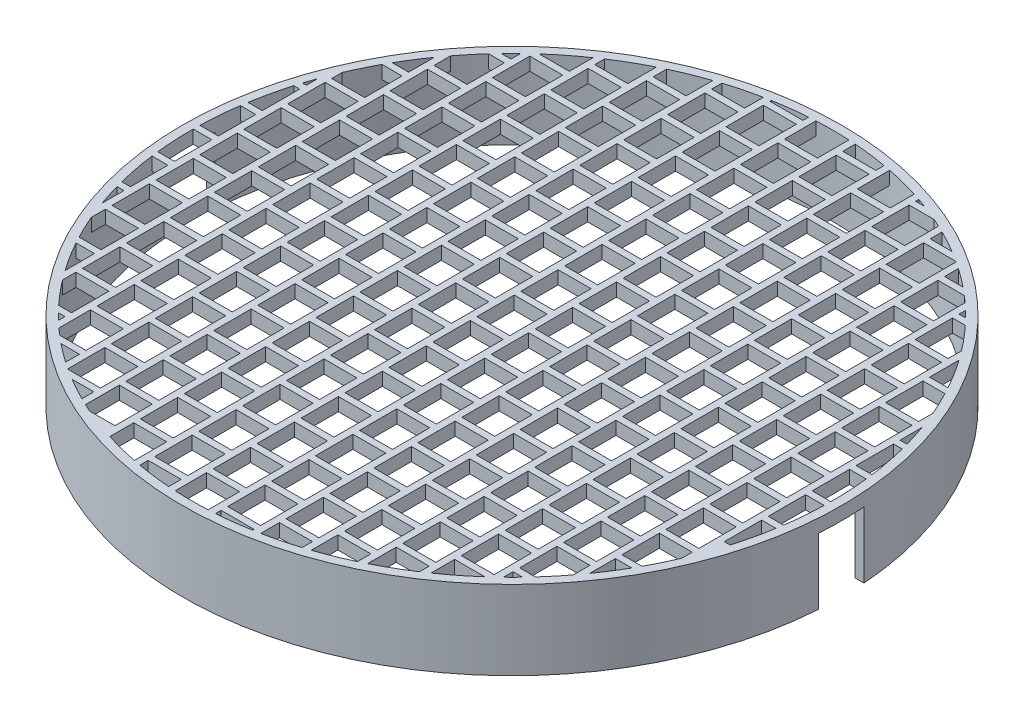
SolidWorks part; units mm, degrees
ref_plane "Front Plane" through (0, 0, 0) normal (0, 0, 1) x (1, 0, 0)
ref_plane "Top Plane" through (0, 0, 0) normal (0, 1, 0) x (1, 0, 0)
ref_plane "Right Plane" through (0, 0, 0) normal (1, 0, 0) x (0, 0, -1)
sketch "Sketch1" plane through (0, 0, 0) normal (0, 1, 0) x (1, 0, 0)
  line L5 (72.8095, 5.2703) -> (74.8146, 5.2703)
  line L6 (-74.8244, -5.1297) -> (-72.8195, -5.1297)
  line L8 (-74.8146, 5.2703) -> (-72.8095, 5.2703)
  line L15 (72.8195, -5.1297) -> (74.8244, -5.1297)
  arc A0 (72.7596, 5.9189) -> (-72.7596, 5.9189) centre (0, 0) ccw
  arc A1 (74.769, 5.8824) -> (-74.769, 5.8824) centre (0, 0) ccw
  arc A2 (-72.7596, -5.9189) -> (72.7596, -5.9189) centre (0, 0) ccw
  arc A3 (-74.769, -5.8824) -> (74.769, -5.8824) centre (0, 0) ccw
  arc A4 (-74.769, 5.8824) -> (-74.8146, 5.2703) centre (0, 0) ccw
  arc A5 (-72.7596, 5.9189) -> (-72.8095, 5.2703) centre (0, 0) ccw
  arc A6 (72.7596, 5.9189) -> (72.8095, 5.2703) centre (0, 0) cw
  arc A7 (74.769, 5.8824) -> (74.8146, 5.2703) centre (0, 0) cw
  arc A8 (-74.8244, -5.1297) -> (-74.769, -5.8824) centre (0, 0) ccw
  arc A9 (-72.8195, -5.1297) -> (-72.7596, -5.9189) centre (0, 0) ccw
  arc A10 (72.8195, -5.1297) -> (72.7596, -5.9189) centre (0, 0) cw
  arc A11 (74.8244, -5.1297) -> (74.769, -5.8824) centre (0, 0) cw
  dimension "D1" = 146
  dimension "D2" = 150
  dimension "D3" = 10.4
extrude "Boss-Extrude1" add sketch "Sketch1" along normal blind 15 and the other way blind 3
sketch "Sketch2" plane through (0, 15, 0) normal (0, 1, 0) x (1, 0, 0)
  line L0 (5.3131, 8.4762) -> (12.8131, 8.4762) [skipped]
  line L1 (-3.75, 4.25) -> (3.75, 4.25)
  line L2 (-3.75, 4.25) -> (-3.75, -4.25)
  line L3 (-3.75, -4.25) -> (3.75, -4.25)
  line L4 (3.75, 4.25) -> (3.75, -4.25)
  line L5 (-3.75, 4.25) -> (3.75, -4.25) construction
  line L6 (-3.75, -4.25) -> (3.75, 4.25) construction
  line L7 (5.3131, 8.4762) -> (5.3131, -0.0238) [skipped]
  line L8 (5.3131, -0.0238) -> (12.8131, -0.0238) [skipped]
  line L9 (12.8131, 8.4762) -> (12.8131, -0.0238) [skipped]
  line L10 (5.3131, 8.4762) -> (12.8131, -0.0238) construction
  line L11 (5.3131, -0.0238) -> (12.8131, 8.4762) construction
  line L12 (14.3762, 12.7024) -> (21.8762, 12.7024) [skipped]
  line L13 (14.3762, 12.7024) -> (14.3762, 4.2024) [skipped]
  line L14 (14.3762, 4.2024) -> (21.8762, 4.2024) [skipped]
  line L15 (21.8762, 12.7024) -> (21.8762, 4.2024) [skipped]
  line L16 (14.3762, 12.7024) -> (21.8762, 4.2024) construction
  line L17 (14.3762, 4.2024) -> (21.8762, 12.7024) construction
  line L18 (23.4392, 16.9285) -> (30.9392, 16.9285) [skipped]
  line L19 (23.4392, 16.9285) -> (23.4392, 8.4285) [skipped]
  line L20 (23.4392, 8.4285) -> (30.9392, 8.4285) [skipped]
  line L21 (30.9392, 16.9285) -> (30.9392, 8.4285) [skipped]
  line L22 (23.4392, 16.9285) -> (30.9392, 8.4285) construction
  line L23 (23.4392, 8.4285) -> (30.9392, 16.9285) construction
  line L24 (32.5023, 21.1547) -> (40.0023, 21.1547) [skipped]
  line L25 (32.5023, 21.1547) -> (32.5023, 12.6547) [skipped]
  line L26 (32.5023, 12.6547) -> (40.0023, 12.6547) [skipped]
  line L27 (40.0023, 21.1547) -> (40.0023, 12.6547) [skipped]
  line L28 (32.5023, 21.1547) -> (40.0023, 12.6547) construction
  line L29 (32.5023, 12.6547) -> (40.0023, 21.1547) construction
  line L30 (41.5654, 25.3809) -> (49.0654, 25.3809) [skipped]
  line L31 (41.5654, 25.3809) -> (41.5654, 16.8809) [skipped]
  line L32 (41.5654, 16.8809) -> (49.0654, 16.8809) [skipped]
  line L33 (49.0654, 25.3809) -> (49.0654, 16.8809) [skipped]
  line L34 (41.5654, 25.3809) -> (49.0654, 16.8809) construction
  line L35 (41.5654, 16.8809) -> (49.0654, 25.3809) construction
  line L36 (50.6285, 29.6071) -> (58.1285, 29.6071) [skipped]
  line L37 (50.6285, 29.6071) -> (50.6285, 21.1071) [skipped]
  line L38 (50.6285, 21.1071) -> (58.1285, 21.1071) [skipped]
  line L39 (58.1285, 29.6071) -> (58.1285, 21.1071) [skipped]
  line L40 (50.6285, 29.6071) -> (58.1285, 21.1071) construction
  line L41 (50.6285, 21.1071) -> (58.1285, 29.6071) construction
  line L42 (59.6915, 33.8333) -> (67.1915, 33.8333) [skipped]
  line L43 (59.6915, 33.8333) -> (59.6915, 25.3333) [skipped]
  line L44 (59.6915, 25.3333) -> (67.1915, 25.3333) [skipped]
  line L45 (67.1915, 33.8333) -> (67.1915, 25.3333) [skipped]
  line L46 (59.6915, 33.8333) -> (67.1915, 25.3333) construction
  line L47 (59.6915, 25.3333) -> (67.1915, 33.8333) construction
  line L48 (5.3131, 18.4762) -> (12.8131, 18.4762)
  line L49 (5.3131, 18.4762) -> (5.3131, 9.9762)
  line L50 (5.3131, 9.9762) -> (12.8131, 9.9762)
  line L51 (12.8131, 18.4762) -> (12.8131, 9.9762)
  line L52 (5.3131, 18.4762) -> (12.8131, 9.9762) construction
  line L53 (5.3131, 9.9762) -> (12.8131, 18.4762) construction
  line L54 (14.3762, 22.7024) -> (21.8762, 22.7024)
  line L55 (14.3762, 22.7024) -> (14.3762, 14.2024)
  line L56 (14.3762, 14.2024) -> (21.8762, 14.2024)
  line L57 (21.8762, 22.7024) -> (21.8762, 14.2024)
  line L58 (14.3762, 22.7024) -> (21.8762, 14.2024) construction
  line L59 (14.3762, 14.2024) -> (21.8762, 22.7024) construction
  line L60 (23.4392, 26.9285) -> (30.9392, 26.9285)
  line L61 (23.4392, 26.9285) -> (23.4392, 18.4285)
  line L62 (23.4392, 18.4285) -> (30.9392, 18.4285)
  line L63 (30.9392, 26.9285) -> (30.9392, 18.4285)
  line L64 (23.4392, 26.9285) -> (30.9392, 18.4285) construction
  line L65 (23.4392, 18.4285) -> (30.9392, 26.9285) construction
  line L66 (32.5023, 31.1547) -> (40.0023, 31.1547)
  line L67 (32.5023, 31.1547) -> (32.5023, 22.6547)
  line L68 (32.5023, 22.6547) -> (40.0023, 22.6547)
  line L69 (40.0023, 31.1547) -> (40.0023, 22.6547)
  line L70 (32.5023, 31.1547) -> (40.0023, 22.6547) construction
  line L71 (32.5023, 22.6547) -> (40.0023, 31.1547) construction
  line L72 (41.5654, 35.3809) -> (49.0654, 35.3809)
  line L73 (41.5654, 35.3809) -> (41.5654, 26.8809)
  line L74 (41.5654, 26.8809) -> (49.0654, 26.8809)
  line L75 (49.0654, 35.3809) -> (49.0654, 26.8809)
  line L76 (41.5654, 35.3809) -> (49.0654, 26.8809) construction
  line L77 (41.5654, 26.8809) -> (49.0654, 35.3809) construction
  line L78 (50.6285, 39.6071) -> (58.1285, 39.6071)
  line L79 (50.6285, 39.6071) -> (50.6285, 31.1071)
  line L80 (50.6285, 31.1071) -> (58.1285, 31.1071)
  line L81 (58.1285, 39.6071) -> (58.1285, 31.1071)
  line L82 (50.6285, 39.6071) -> (58.1285, 31.1071) construction
  line L83 (50.6285, 31.1071) -> (58.1285, 39.6071) construction
  line L84 (59.6915, 43.8333) -> (67.1915, 43.8333)
  line L85 (59.6915, 43.8333) -> (59.6915, 35.3333)
  line L86 (59.6915, 35.3333) -> (67.1915, 35.3333)
  line L87 (67.1915, 43.8333) -> (67.1915, 35.3333)
  line L88 (59.6915, 43.8333) -> (67.1915, 35.3333) construction
  line L89 (59.6915, 35.3333) -> (67.1915, 43.8333) construction
  line L90 (5.3131, 28.4762) -> (12.8131, 28.4762)
  line L91 (5.3131, 28.4762) -> (5.3131, 19.9762)
  line L92 (5.3131, 19.9762) -> (12.8131, 19.9762)
  line L93 (12.8131, 28.4762) -> (12.8131, 19.9762)
  line L94 (5.3131, 28.4762) -> (12.8131, 19.9762) construction
  line L95 (5.3131, 19.9762) -> (12.8131, 28.4762) construction
  line L96 (14.3762, 32.7024) -> (21.8762, 32.7024)
  line L97 (14.3762, 32.7024) -> (14.3762, 24.2024)
  line L98 (14.3762, 24.2024) -> (21.8762, 24.2024)
  line L99 (21.8762, 32.7024) -> (21.8762, 24.2024)
  line L100 (14.3762, 32.7024) -> (21.8762, 24.2024) construction
  line L101 (14.3762, 24.2024) -> (21.8762, 32.7024) construction
  line L102 (23.4392, 36.9285) -> (30.9392, 36.9285)
  line L103 (23.4392, 36.9285) -> (23.4392, 28.4285)
  line L104 (23.4392, 28.4285) -> (30.9392, 28.4285)
  line L105 (30.9392, 36.9285) -> (30.9392, 28.4285)
  line L106 (23.4392, 36.9285) -> (30.9392, 28.4285) construction
  line L107 (23.4392, 28.4285) -> (30.9392, 36.9285) construction
  line L108 (32.5023, 41.1547) -> (40.0023, 41.1547)
  line L109 (32.5023, 41.1547) -> (32.5023, 32.6547)
  line L110 (32.5023, 32.6547) -> (40.0023, 32.6547)
  line L111 (40.0023, 41.1547) -> (40.0023, 32.6547)
  line L112 (32.5023, 41.1547) -> (40.0023, 32.6547) construction
  line L113 (32.5023, 32.6547) -> (40.0023, 41.1547) construction
  line L114 (41.5654, 45.3809) -> (49.0654, 45.3809)
  line L115 (41.5654, 45.3809) -> (41.5654, 36.8809)
  line L116 (41.5654, 36.8809) -> (49.0654, 36.8809)
  line L117 (49.0654, 45.3809) -> (49.0654, 36.8809)
  line L118 (41.5654, 45.3809) -> (49.0654, 36.8809) construction
  line L119 (41.5654, 36.8809) -> (49.0654, 45.3809) construction
  line L120 (50.6285, 49.6071) -> (58.1285, 49.6071)
  line L121 (50.6285, 49.6071) -> (50.6285, 41.1071)
  line L122 (50.6285, 41.1071) -> (58.1285, 41.1071)
  line L123 (58.1285, 49.6071) -> (58.1285, 41.1071)
  line L124 (50.6285, 49.6071) -> (58.1285, 41.1071) construction
  line L125 (50.6285, 41.1071) -> (58.1285, 49.6071) construction
  line L132 (5.3131, 38.4762) -> (12.8131, 38.4762)
  line L133 (5.3131, 38.4762) -> (5.3131, 29.9762)
  line L134 (5.3131, 29.9762) -> (12.8131, 29.9762)
  line L135 (12.8131, 38.4762) -> (12.8131, 29.9762)
  line L136 (5.3131, 38.4762) -> (12.8131, 29.9762) construction
  line L137 (5.3131, 29.9762) -> (12.8131, 38.4762) construction
  line L138 (14.3762, 42.7024) -> (21.8762, 42.7024)
  line L139 (14.3762, 42.7024) -> (14.3762, 34.2024)
  line L140 (14.3762, 34.2024) -> (21.8762, 34.2024)
  line L141 (21.8762, 42.7024) -> (21.8762, 34.2024)
  line L142 (14.3762, 42.7024) -> (21.8762, 34.2024) construction
  line L143 (14.3762, 34.2024) -> (21.8762, 42.7024) construction
  line L144 (23.4392, 46.9285) -> (30.9392, 46.9285)
  line L145 (23.4392, 46.9285) -> (23.4392, 38.4285)
  line L146 (23.4392, 38.4285) -> (30.9392, 38.4285)
  line L147 (30.9392, 46.9285) -> (30.9392, 38.4285)
  line L148 (23.4392, 46.9285) -> (30.9392, 38.4285) construction
  line L149 (23.4392, 38.4285) -> (30.9392, 46.9285) construction
  line L150 (32.5023, 51.1547) -> (40.0023, 51.1547)
  line L151 (32.5023, 51.1547) -> (32.5023, 42.6547)
  line L152 (32.5023, 42.6547) -> (40.0023, 42.6547)
  line L153 (40.0023, 51.1547) -> (40.0023, 42.6547)
  line L154 (32.5023, 51.1547) -> (40.0023, 42.6547) construction
  line L155 (32.5023, 42.6547) -> (40.0023, 51.1547) construction
  line L156 (41.5654, 55.3809) -> (49.0654, 55.3809)
  line L157 (41.5654, 55.3809) -> (41.5654, 46.8809)
  line L158 (41.5654, 46.8809) -> (49.0654, 46.8809)
  line L159 (49.0654, 55.3809) -> (49.0654, 46.8809)
  line L160 (41.5654, 55.3809) -> (49.0654, 46.8809) construction
  line L161 (41.5654, 46.8809) -> (49.0654, 55.3809) construction
  line L162 (50.6285, 59.6071) -> (58.1285, 59.6071)
  line L163 (50.6285, 59.6071) -> (50.6285, 51.1071)
  line L164 (50.6285, 51.1071) -> (58.1285, 51.1071)
  line L165 (58.1285, 59.6071) -> (58.1285, 51.1071)
  line L166 (50.6285, 59.6071) -> (58.1285, 51.1071) construction
  line L167 (50.6285, 51.1071) -> (58.1285, 59.6071) construction
  line L174 (5.3131, 48.4762) -> (12.8131, 48.4762)
  line L175 (5.3131, 48.4762) -> (5.3131, 39.9762)
  line L176 (5.3131, 39.9762) -> (12.8131, 39.9762)
  line L177 (12.8131, 48.4762) -> (12.8131, 39.9762)
  line L178 (5.3131, 48.4762) -> (12.8131, 39.9762) construction
  line L179 (5.3131, 39.9762) -> (12.8131, 48.4762) construction
  line L180 (14.3762, 52.7024) -> (21.8762, 52.7024)
  line L181 (14.3762, 52.7024) -> (14.3762, 44.2024)
  line L182 (14.3762, 44.2024) -> (21.8762, 44.2024)
  line L183 (21.8762, 52.7024) -> (21.8762, 44.2024)
  line L184 (14.3762, 52.7024) -> (21.8762, 44.2024) construction
  line L185 (14.3762, 44.2024) -> (21.8762, 52.7024) construction
  line L186 (23.4392, 56.9285) -> (30.9392, 56.9285)
  line L187 (23.4392, 56.9285) -> (23.4392, 48.4285)
  line L188 (23.4392, 48.4285) -> (30.9392, 48.4285)
  line L189 (30.9392, 56.9285) -> (30.9392, 48.4285)
  line L190 (23.4392, 56.9285) -> (30.9392, 48.4285) construction
  line L191 (23.4392, 48.4285) -> (30.9392, 56.9285) construction
  line L192 (32.5023, 61.1547) -> (40.0023, 61.1547)
  line L193 (32.5023, 61.1547) -> (32.5023, 52.6547)
  line L194 (32.5023, 52.6547) -> (40.0023, 52.6547)
  line L195 (40.0023, 61.1547) -> (40.0023, 52.6547)
  line L196 (32.5023, 61.1547) -> (40.0023, 52.6547) construction
  line L197 (32.5023, 52.6547) -> (40.0023, 61.1547) construction
  line L198 (41.5654, 65.3809) -> (49.0654, 65.3809)
  line L199 (41.5654, 65.3809) -> (41.5654, 56.8809)
  line L200 (41.5654, 56.8809) -> (49.0654, 56.8809)
  line L201 (49.0654, 65.3809) -> (49.0654, 56.8809)
  line L202 (41.5654, 65.3809) -> (49.0654, 56.8809) construction
  line L203 (41.5654, 56.8809) -> (49.0654, 65.3809) construction
  line L216 (5.3131, 58.4762) -> (12.8131, 58.4762)
  line L217 (5.3131, 58.4762) -> (5.3131, 49.9762)
  line L218 (5.3131, 49.9762) -> (12.8131, 49.9762)
  line L219 (12.8131, 58.4762) -> (12.8131, 49.9762)
  line L220 (5.3131, 58.4762) -> (12.8131, 49.9762) construction
  line L221 (5.3131, 49.9762) -> (12.8131, 58.4762) construction
  line L222 (14.3762, 62.7024) -> (21.8762, 62.7024)
  line L223 (14.3762, 62.7024) -> (14.3762, 54.2024)
  line L224 (14.3762, 54.2024) -> (21.8762, 54.2024)
  line L225 (21.8762, 62.7024) -> (21.8762, 54.2024)
  line L226 (14.3762, 62.7024) -> (21.8762, 54.2024) construction
  line L227 (14.3762, 54.2024) -> (21.8762, 62.7024) construction
  line L228 (23.4392, 66.9285) -> (30.9392, 66.9285)
  line L229 (23.4392, 66.9285) -> (23.4392, 58.4285)
  line L230 (23.4392, 58.4285) -> (30.9392, 58.4285)
  line L231 (30.9392, 66.9285) -> (30.9392, 58.4285)
  line L232 (23.4392, 66.9285) -> (30.9392, 58.4285) construction
  line L233 (23.4392, 58.4285) -> (30.9392, 66.9285) construction
  line L234 (32.5023, 71.1547) -> (40.0023, 71.1547)
  line L235 (32.5023, 71.1547) -> (32.5023, 62.6547)
  line L236 (32.5023, 62.6547) -> (40.0023, 62.6547)
  line L237 (40.0023, 71.1547) -> (40.0023, 62.6547)
  line L238 (32.5023, 71.1547) -> (40.0023, 62.6547) construction
  line L239 (32.5023, 62.6547) -> (40.0023, 71.1547) construction
  line L258 (5.3131, 68.4762) -> (12.8131, 68.4762)
  line L259 (5.3131, 68.4762) -> (5.3131, 59.9762)
  line L260 (5.3131, 59.9762) -> (12.8131, 59.9762)
  line L261 (12.8131, 68.4762) -> (12.8131, 59.9762)
  line L262 (5.3131, 68.4762) -> (12.8131, 59.9762) construction
  line L263 (5.3131, 59.9762) -> (12.8131, 68.4762) construction
  line L264 (14.3762, 72.7024) -> (21.8762, 72.7024)
  line L265 (14.3762, 72.7024) -> (14.3762, 64.2024)
  line L266 (14.3762, 64.2024) -> (21.8762, 64.2024)
  line L267 (21.8762, 72.7024) -> (21.8762, 64.2024)
  line L268 (14.3762, 72.7024) -> (21.8762, 64.2024) construction
  line L269 (14.3762, 64.2024) -> (21.8762, 72.7024) construction
  line L270 (23.4392, 76.9285) -> (30.9392, 76.9285)
  line L271 (23.4392, 76.9285) -> (23.4392, 68.4285)
  line L272 (23.4392, 68.4285) -> (30.9392, 68.4285)
  line L273 (30.9392, 76.9285) -> (30.9392, 68.4285)
  line L274 (23.4392, 76.9285) -> (30.9392, 68.4285) construction
  line L275 (23.4392, 68.4285) -> (30.9392, 76.9285) construction
  line L300 (5.3131, 78.4762) -> (12.8131, 78.4762)
  line L301 (5.3131, 78.4762) -> (5.3131, 69.9762)
  line L302 (5.3131, 69.9762) -> (12.8131, 69.9762)
  line L303 (12.8131, 78.4762) -> (12.8131, 69.9762)
  line L304 (5.3131, 78.4762) -> (12.8131, 69.9762) construction
  line L305 (5.3131, 69.9762) -> (12.8131, 78.4762) construction
  line L342 (-3.75, 14.25) -> (3.75, 14.25) [skipped]
  line L343 (-3.75, 14.25) -> (-3.75, 5.75) [skipped]
  line L344 (-3.75, 5.75) -> (3.75, 5.75) [skipped]
  line L345 (3.75, 14.25) -> (3.75, 5.75) [skipped]
  line L346 (-3.75, 14.25) -> (3.75, 5.75) construction
  line L347 (-3.75, 5.75) -> (3.75, 14.25) construction
  line L348 (-3.75, 24.25) -> (3.75, 24.25) [skipped]
  line L349 (-3.75, 24.25) -> (-3.75, 15.75) [skipped]
  line L350 (-3.75, 15.75) -> (3.75, 15.75) [skipped]
  line L351 (3.75, 24.25) -> (3.75, 15.75) [skipped]
  line L352 (-3.75, 24.25) -> (3.75, 15.75) construction
  line L353 (-3.75, 15.75) -> (3.75, 24.25) construction
  line L354 (-3.75, 34.25) -> (3.75, 34.25) [skipped]
  line L355 (-3.75, 34.25) -> (-3.75, 25.75) [skipped]
  line L356 (-3.75, 25.75) -> (3.75, 25.75) [skipped]
  line L357 (3.75, 34.25) -> (3.75, 25.75) [skipped]
  line L358 (-3.75, 34.25) -> (3.75, 25.75) construction
  line L359 (-3.75, 25.75) -> (3.75, 34.25) construction
  line L360 (-3.75, 44.25) -> (3.75, 44.25) [skipped]
  line L361 (-3.75, 44.25) -> (-3.75, 35.75) [skipped]
  line L362 (-3.75, 35.75) -> (3.75, 35.75) [skipped]
  line L363 (3.75, 44.25) -> (3.75, 35.75) [skipped]
  line L364 (-3.75, 44.25) -> (3.75, 35.75) construction
  line L365 (-3.75, 35.75) -> (3.75, 44.25) construction
  line L366 (-3.75, 54.25) -> (3.75, 54.25) [skipped]
  line L367 (-3.75, 54.25) -> (-3.75, 45.75) [skipped]
  line L368 (-3.75, 45.75) -> (3.75, 45.75) [skipped]
  line L369 (3.75, 54.25) -> (3.75, 45.75) [skipped]
  line L370 (-3.75, 54.25) -> (3.75, 45.75) construction
  line L371 (-3.75, 45.75) -> (3.75, 54.25) construction
  line L372 (-3.75, 64.25) -> (3.75, 64.25) [skipped]
  line L373 (-3.75, 64.25) -> (-3.75, 55.75) [skipped]
  line L374 (-3.75, 55.75) -> (3.75, 55.75) [skipped]
  line L375 (3.75, 64.25) -> (3.75, 55.75) [skipped]
  line L376 (-3.75, 64.25) -> (3.75, 55.75) construction
  line L377 (-3.75, 55.75) -> (3.75, 64.25) construction
  line L378 (-3.75, 74.25) -> (3.75, 74.25) [skipped]
  line L379 (-3.75, 74.25) -> (-3.75, 65.75) [skipped]
  line L380 (-3.75, 65.75) -> (3.75, 65.75) [skipped]
  line L381 (3.75, 74.25) -> (3.75, 65.75) [skipped]
  line L382 (-3.75, 74.25) -> (3.75, 65.75) construction
  line L383 (-3.75, 65.75) -> (3.75, 74.25) construction
  line L384 (5.3131, 8.4762) -> (12.8131, 8.4762)
  line L385 (5.3131, 8.4762) -> (5.3131, -0.0238)
  line L386 (5.3131, -0.0238) -> (12.8131, -0.0238)
  line L387 (12.8131, 8.4762) -> (12.8131, -0.0238)
  line L388 (5.3131, 8.4762) -> (12.8131, -0.0238) construction
  line L389 (5.3131, -0.0238) -> (12.8131, 8.4762) construction
  line L390 (14.3762, 12.7024) -> (21.8762, 12.7024)
  line L391 (14.3762, 12.7024) -> (14.3762, 4.2024)
  line L392 (14.3762, 4.2024) -> (21.8762, 4.2024)
  line L393 (21.8762, 12.7024) -> (21.8762, 4.2024)
  line L394 (14.3762, 12.7024) -> (21.8762, 4.2024) construction
  line L395 (14.3762, 4.2024) -> (21.8762, 12.7024) construction
  line L396 (23.4392, 16.9285) -> (30.9392, 16.9285)
  line L397 (23.4392, 16.9285) -> (23.4392, 8.4285)
  line L398 (23.4392, 8.4285) -> (30.9392, 8.4285)
  line L399 (30.9392, 16.9285) -> (30.9392, 8.4285)
  line L400 (23.4392, 16.9285) -> (30.9392, 8.4285) construction
  line L401 (23.4392, 8.4285) -> (30.9392, 16.9285) construction
  line L402 (32.5023, 21.1547) -> (40.0023, 21.1547)
  line L403 (32.5023, 21.1547) -> (32.5023, 12.6547)
  line L404 (32.5023, 12.6547) -> (40.0023, 12.6547)
  line L405 (40.0023, 21.1547) -> (40.0023, 12.6547)
  line L406 (32.5023, 21.1547) -> (40.0023, 12.6547) construction
  line L407 (32.5023, 12.6547) -> (40.0023, 21.1547) construction
  line L408 (41.5654, 25.3809) -> (49.0654, 25.3809)
  line L409 (41.5654, 25.3809) -> (41.5654, 16.8809)
  line L410 (41.5654, 16.8809) -> (49.0654, 16.8809)
  line L411 (49.0654, 25.3809) -> (49.0654, 16.8809)
  line L412 (41.5654, 25.3809) -> (49.0654, 16.8809) construction
  line L413 (41.5654, 16.8809) -> (49.0654, 25.3809) construction
  line L414 (50.6285, 29.6071) -> (58.1285, 29.6071)
  line L415 (50.6285, 29.6071) -> (50.6285, 21.1071)
  line L416 (50.6285, 21.1071) -> (58.1285, 21.1071)
  line L417 (58.1285, 29.6071) -> (58.1285, 21.1071)
  line L418 (50.6285, 29.6071) -> (58.1285, 21.1071) construction
  line L419 (50.6285, 21.1071) -> (58.1285, 29.6071) construction
  line L420 (59.6915, 33.8333) -> (67.1915, 33.8333)
  line L421 (59.6915, 33.8333) -> (59.6915, 25.3333)
  line L422 (59.6915, 25.3333) -> (67.1915, 25.3333)
  line L423 (67.1915, 33.8333) -> (67.1915, 25.3333)
  line L424 (59.6915, 33.8333) -> (67.1915, 25.3333) construction
  line L425 (59.6915, 25.3333) -> (67.1915, 33.8333) construction
  line L432 (5.3131, -1.5238) -> (12.8131, -1.5238)
  line L433 (5.3131, -1.5238) -> (5.3131, -10.0238)
  line L434 (5.3131, -10.0238) -> (12.8131, -10.0238)
  line L435 (12.8131, -1.5238) -> (12.8131, -10.0238)
  line L436 (5.3131, -1.5238) -> (12.8131, -10.0238) construction
  line L437 (5.3131, -10.0238) -> (12.8131, -1.5238) construction
  line L438 (14.3762, 2.7024) -> (21.8762, 2.7024)
  line L439 (14.3762, 2.7024) -> (14.3762, -5.7976)
  line L440 (14.3762, -5.7976) -> (21.8762, -5.7976)
  line L441 (21.8762, 2.7024) -> (21.8762, -5.7976)
  line L442 (14.3762, 2.7024) -> (21.8762, -5.7976) construction
  line L443 (14.3762, -5.7976) -> (21.8762, 2.7024) construction
  line L444 (23.4392, 6.9285) -> (30.9392, 6.9285)
  line L445 (23.4392, 6.9285) -> (23.4392, -1.5715)
  line L446 (23.4392, -1.5715) -> (30.9392, -1.5715)
  line L447 (30.9392, 6.9285) -> (30.9392, -1.5715)
  line L448 (23.4392, 6.9285) -> (30.9392, -1.5715) construction
  line L449 (23.4392, -1.5715) -> (30.9392, 6.9285) construction
  line L450 (32.5023, 11.1547) -> (40.0023, 11.1547)
  line L451 (32.5023, 11.1547) -> (32.5023, 2.6547)
  line L452 (32.5023, 2.6547) -> (40.0023, 2.6547)
  line L453 (40.0023, 11.1547) -> (40.0023, 2.6547)
  line L454 (32.5023, 11.1547) -> (40.0023, 2.6547) construction
  line L455 (32.5023, 2.6547) -> (40.0023, 11.1547) construction
  line L456 (41.5654, 15.3809) -> (49.0654, 15.3809)
  line L457 (41.5654, 15.3809) -> (41.5654, 6.8809)
  line L458 (41.5654, 6.8809) -> (49.0654, 6.8809)
  line L459 (49.0654, 15.3809) -> (49.0654, 6.8809)
  line L460 (41.5654, 15.3809) -> (49.0654, 6.8809) construction
  line L461 (41.5654, 6.8809) -> (49.0654, 15.3809) construction
  line L462 (50.6285, 19.6071) -> (58.1285, 19.6071)
  line L463 (50.6285, 19.6071) -> (50.6285, 11.1071)
  line L464 (50.6285, 11.1071) -> (58.1285, 11.1071)
  line L465 (58.1285, 19.6071) -> (58.1285, 11.1071)
  line L466 (50.6285, 19.6071) -> (58.1285, 11.1071) construction
  line L467 (50.6285, 11.1071) -> (58.1285, 19.6071) construction
  line L468 (59.6915, 23.8333) -> (67.1915, 23.8333)
  line L469 (59.6915, 23.8333) -> (59.6915, 15.3333)
  line L470 (59.6915, 15.3333) -> (67.1915, 15.3333)
  line L471 (67.1915, 23.8333) -> (67.1915, 15.3333)
  line L472 (59.6915, 23.8333) -> (67.1915, 15.3333) construction
  line L473 (59.6915, 15.3333) -> (67.1915, 23.8333) construction
  line L474 (68.7546, 28.0595) -> (76.2546, 28.0595)
  line L475 (68.7546, 28.0595) -> (68.7546, 19.5595)
  line L476 (68.7546, 19.5595) -> (76.2546, 19.5595)
  line L477 (76.2546, 28.0595) -> (76.2546, 19.5595)
  line L478 (68.7546, 28.0595) -> (76.2546, 19.5595) construction
  line L479 (68.7546, 19.5595) -> (76.2546, 28.0595) construction
  line L480 (5.3131, -11.5238) -> (12.8131, -11.5238)
  line L481 (5.3131, -11.5238) -> (5.3131, -20.0238)
  line L482 (5.3131, -20.0238) -> (12.8131, -20.0238)
  line L483 (12.8131, -11.5238) -> (12.8131, -20.0238)
  line L484 (5.3131, -11.5238) -> (12.8131, -20.0238) construction
  line L485 (5.3131, -20.0238) -> (12.8131, -11.5238) construction
  line L486 (14.3762, -7.2976) -> (21.8762, -7.2976)
  line L487 (14.3762, -7.2976) -> (14.3762, -15.7976)
  line L488 (14.3762, -15.7976) -> (21.8762, -15.7976)
  line L489 (21.8762, -7.2976) -> (21.8762, -15.7976)
  line L490 (14.3762, -7.2976) -> (21.8762, -15.7976) construction
  line L491 (14.3762, -15.7976) -> (21.8762, -7.2976) construction
  line L492 (23.4392, -3.0715) -> (30.9392, -3.0715)
  line L493 (23.4392, -3.0715) -> (23.4392, -11.5715)
  line L494 (23.4392, -11.5715) -> (30.9392, -11.5715)
  line L495 (30.9392, -3.0715) -> (30.9392, -11.5715)
  line L496 (23.4392, -3.0715) -> (30.9392, -11.5715) construction
  line L497 (23.4392, -11.5715) -> (30.9392, -3.0715) construction
  line L498 (32.5023, 1.1547) -> (40.0023, 1.1547)
  line L499 (32.5023, 1.1547) -> (32.5023, -7.3453)
  line L500 (32.5023, -7.3453) -> (40.0023, -7.3453)
  line L501 (40.0023, 1.1547) -> (40.0023, -7.3453)
  line L502 (32.5023, 1.1547) -> (40.0023, -7.3453) construction
  line L503 (32.5023, -7.3453) -> (40.0023, 1.1547) construction
  line L504 (41.5654, 5.3809) -> (49.0654, 5.3809)
  line L505 (41.5654, 5.3809) -> (41.5654, -3.1191)
  line L506 (41.5654, -3.1191) -> (49.0654, -3.1191)
  line L507 (49.0654, 5.3809) -> (49.0654, -3.1191)
  line L508 (41.5654, 5.3809) -> (49.0654, -3.1191) construction
  line L509 (41.5654, -3.1191) -> (49.0654, 5.3809) construction
  line L510 (50.6285, 9.6071) -> (58.1285, 9.6071)
  line L511 (50.6285, 9.6071) -> (50.6285, 1.1071)
  line L512 (50.6285, 1.1071) -> (58.1285, 1.1071)
  line L513 (58.1285, 9.6071) -> (58.1285, 1.1071)
  line L514 (50.6285, 9.6071) -> (58.1285, 1.1071) construction
  line L515 (50.6285, 1.1071) -> (58.1285, 9.6071) construction
  line L516 (59.6915, 13.8333) -> (67.1915, 13.8333)
  line L517 (59.6915, 13.8333) -> (59.6915, 5.3333)
  line L518 (59.6915, 5.3333) -> (67.1915, 5.3333)
  line L519 (67.1915, 13.8333) -> (67.1915, 5.3333)
  line L520 (59.6915, 13.8333) -> (67.1915, 5.3333) construction
  line L521 (59.6915, 5.3333) -> (67.1915, 13.8333) construction
  line L522 (68.7546, 18.0595) -> (76.2546, 18.0595)
  line L523 (68.7546, 18.0595) -> (68.7546, 9.5595)
  line L524 (68.7546, 9.5595) -> (76.2546, 9.5595)
  line L525 (76.2546, 18.0595) -> (76.2546, 9.5595)
  line L526 (68.7546, 18.0595) -> (76.2546, 9.5595) construction
  line L527 (68.7546, 9.5595) -> (76.2546, 18.0595) construction
  line L528 (5.3131, -21.5238) -> (12.8131, -21.5238)
  line L529 (5.3131, -21.5238) -> (5.3131, -30.0238)
  line L530 (5.3131, -30.0238) -> (12.8131, -30.0238)
  line L531 (12.8131, -21.5238) -> (12.8131, -30.0238)
  line L532 (5.3131, -21.5238) -> (12.8131, -30.0238) construction
  line L533 (5.3131, -30.0238) -> (12.8131, -21.5238) construction
  line L534 (14.3762, -17.2976) -> (21.8762, -17.2976)
  line L535 (14.3762, -17.2976) -> (14.3762, -25.7976)
  line L536 (14.3762, -25.7976) -> (21.8762, -25.7976)
  line L537 (21.8762, -17.2976) -> (21.8762, -25.7976)
  line L538 (14.3762, -17.2976) -> (21.8762, -25.7976) construction
  line L539 (14.3762, -25.7976) -> (21.8762, -17.2976) construction
  line L540 (23.4392, -13.0715) -> (30.9392, -13.0715)
  line L541 (23.4392, -13.0715) -> (23.4392, -21.5715)
  line L542 (23.4392, -21.5715) -> (30.9392, -21.5715)
  line L543 (30.9392, -13.0715) -> (30.9392, -21.5715)
  line L544 (23.4392, -13.0715) -> (30.9392, -21.5715) construction
  line L545 (23.4392, -21.5715) -> (30.9392, -13.0715) construction
  line L546 (32.5023, -8.8453) -> (40.0023, -8.8453)
  line L547 (32.5023, -8.8453) -> (32.5023, -17.3453)
  line L548 (32.5023, -17.3453) -> (40.0023, -17.3453)
  line L549 (40.0023, -8.8453) -> (40.0023, -17.3453)
  line L550 (32.5023, -8.8453) -> (40.0023, -17.3453) construction
  line L551 (32.5023, -17.3453) -> (40.0023, -8.8453) construction
  line L552 (41.5654, -4.6191) -> (49.0654, -4.6191)
  line L553 (41.5654, -4.6191) -> (41.5654, -13.1191)
  line L554 (41.5654, -13.1191) -> (49.0654, -13.1191)
  line L555 (49.0654, -4.6191) -> (49.0654, -13.1191)
  line L556 (41.5654, -4.6191) -> (49.0654, -13.1191) construction
  line L557 (41.5654, -13.1191) -> (49.0654, -4.6191) construction
  line L558 (50.6285, -0.3929) -> (58.1285, -0.3929)
  line L559 (50.6285, -0.3929) -> (50.6285, -8.8929)
  line L560 (50.6285, -8.8929) -> (58.1285, -8.8929)
  line L561 (58.1285, -0.3929) -> (58.1285, -8.8929)
  line L562 (50.6285, -0.3929) -> (58.1285, -8.8929) construction
  line L563 (50.6285, -8.8929) -> (58.1285, -0.3929) construction
  line L564 (59.6915, 3.8333) -> (67.1915, 3.8333)
  line L565 (59.6915, 3.8333) -> (59.6915, -4.6667)
  line L566 (59.6915, -4.6667) -> (67.1915, -4.6667)
  line L567 (67.1915, 3.8333) -> (67.1915, -4.6667)
  line L568 (59.6915, 3.8333) -> (67.1915, -4.6667) construction
  line L569 (59.6915, -4.6667) -> (67.1915, 3.8333) construction
  line L570 (68.7546, 8.0595) -> (76.2546, 8.0595)
  line L571 (68.7546, 8.0595) -> (68.7546, -0.4405)
  line L572 (68.7546, -0.4405) -> (76.2546, -0.4405)
  line L573 (76.2546, 8.0595) -> (76.2546, -0.4405)
  line L574 (68.7546, 8.0595) -> (76.2546, -0.4405) construction
  line L575 (68.7546, -0.4405) -> (76.2546, 8.0595) construction
  line L576 (5.3131, -31.5238) -> (12.8131, -31.5238)
  line L577 (5.3131, -31.5238) -> (5.3131, -40.0238)
  line L578 (5.3131, -40.0238) -> (12.8131, -40.0238)
  line L579 (12.8131, -31.5238) -> (12.8131, -40.0238)
  line L580 (5.3131, -31.5238) -> (12.8131, -40.0238) construction
  line L581 (5.3131, -40.0238) -> (12.8131, -31.5238) construction
  line L582 (14.3762, -27.2976) -> (21.8762, -27.2976)
  line L583 (14.3762, -27.2976) -> (14.3762, -35.7976)
  line L584 (14.3762, -35.7976) -> (21.8762, -35.7976)
  line L585 (21.8762, -27.2976) -> (21.8762, -35.7976)
  line L586 (14.3762, -27.2976) -> (21.8762, -35.7976) construction
  line L587 (14.3762, -35.7976) -> (21.8762, -27.2976) construction
  line L588 (23.4392, -23.0715) -> (30.9392, -23.0715)
  line L589 (23.4392, -23.0715) -> (23.4392, -31.5715)
  line L590 (23.4392, -31.5715) -> (30.9392, -31.5715)
  line L591 (30.9392, -23.0715) -> (30.9392, -31.5715)
  line L592 (23.4392, -23.0715) -> (30.9392, -31.5715) construction
  line L593 (23.4392, -31.5715) -> (30.9392, -23.0715) construction
  line L594 (32.5023, -18.8453) -> (40.0023, -18.8453)
  line L595 (32.5023, -18.8453) -> (32.5023, -27.3453)
  line L596 (32.5023, -27.3453) -> (40.0023, -27.3453)
  line L597 (40.0023, -18.8453) -> (40.0023, -27.3453)
  line L598 (32.5023, -18.8453) -> (40.0023, -27.3453) construction
  line L599 (32.5023, -27.3453) -> (40.0023, -18.8453) construction
  line L600 (41.5654, -14.6191) -> (49.0654, -14.6191)
  line L601 (41.5654, -14.6191) -> (41.5654, -23.1191)
  line L602 (41.5654, -23.1191) -> (49.0654, -23.1191)
  line L603 (49.0654, -14.6191) -> (49.0654, -23.1191)
  line L604 (41.5654, -14.6191) -> (49.0654, -23.1191) construction
  line L605 (41.5654, -23.1191) -> (49.0654, -14.6191) construction
  line L606 (50.6285, -10.3929) -> (58.1285, -10.3929)
  line L607 (50.6285, -10.3929) -> (50.6285, -18.8929)
  line L608 (50.6285, -18.8929) -> (58.1285, -18.8929)
  line L609 (58.1285, -10.3929) -> (58.1285, -18.8929)
  line L610 (50.6285, -10.3929) -> (58.1285, -18.8929) construction
  line L611 (50.6285, -18.8929) -> (58.1285, -10.3929) construction
  line L612 (59.6915, -6.1667) -> (67.1915, -6.1667)
  line L613 (59.6915, -6.1667) -> (59.6915, -14.6667)
  line L614 (59.6915, -14.6667) -> (67.1915, -14.6667)
  line L615 (67.1915, -6.1667) -> (67.1915, -14.6667)
  line L616 (59.6915, -6.1667) -> (67.1915, -14.6667) construction
  line L617 (59.6915, -14.6667) -> (67.1915, -6.1667) construction
  line L618 (68.7546, -1.9405) -> (76.2546, -1.9405)
  line L619 (68.7546, -1.9405) -> (68.7546, -10.4405)
  line L620 (68.7546, -10.4405) -> (76.2546, -10.4405)
  line L621 (76.2546, -1.9405) -> (76.2546, -10.4405)
  line L622 (68.7546, -1.9405) -> (76.2546, -10.4405) construction
  line L623 (68.7546, -10.4405) -> (76.2546, -1.9405) construction
  line L624 (5.3131, -41.5238) -> (12.8131, -41.5238)
  line L625 (5.3131, -41.5238) -> (5.3131, -50.0238)
  line L626 (5.3131, -50.0238) -> (12.8131, -50.0238)
  line L627 (12.8131, -41.5238) -> (12.8131, -50.0238)
  line L628 (5.3131, -41.5238) -> (12.8131, -50.0238) construction
  line L629 (5.3131, -50.0238) -> (12.8131, -41.5238) construction
  line L630 (14.3762, -37.2976) -> (21.8762, -37.2976)
  line L631 (14.3762, -37.2976) -> (14.3762, -45.7976)
  line L632 (14.3762, -45.7976) -> (21.8762, -45.7976)
  line L633 (21.8762, -37.2976) -> (21.8762, -45.7976)
  line L634 (14.3762, -37.2976) -> (21.8762, -45.7976) construction
  line L635 (14.3762, -45.7976) -> (21.8762, -37.2976) construction
  line L636 (23.4392, -33.0715) -> (30.9392, -33.0715)
  line L637 (23.4392, -33.0715) -> (23.4392, -41.5715)
  line L638 (23.4392, -41.5715) -> (30.9392, -41.5715)
  line L639 (30.9392, -33.0715) -> (30.9392, -41.5715)
  line L640 (23.4392, -33.0715) -> (30.9392, -41.5715) construction
  line L641 (23.4392, -41.5715) -> (30.9392, -33.0715) construction
  line L642 (32.5023, -28.8453) -> (40.0023, -28.8453)
  line L643 (32.5023, -28.8453) -> (32.5023, -37.3453)
  line L644 (32.5023, -37.3453) -> (40.0023, -37.3453)
  line L645 (40.0023, -28.8453) -> (40.0023, -37.3453)
  line L646 (32.5023, -28.8453) -> (40.0023, -37.3453) construction
  line L647 (32.5023, -37.3453) -> (40.0023, -28.8453) construction
  line L648 (41.5654, -24.6191) -> (49.0654, -24.6191)
  line L649 (41.5654, -24.6191) -> (41.5654, -33.1191)
  line L650 (41.5654, -33.1191) -> (49.0654, -33.1191)
  line L651 (49.0654, -24.6191) -> (49.0654, -33.1191)
  line L652 (41.5654, -24.6191) -> (49.0654, -33.1191) construction
  line L653 (41.5654, -33.1191) -> (49.0654, -24.6191) construction
  line L654 (50.6285, -20.3929) -> (58.1285, -20.3929)
  line L655 (50.6285, -20.3929) -> (50.6285, -28.8929)
  line L656 (50.6285, -28.8929) -> (58.1285, -28.8929)
  line L657 (58.1285, -20.3929) -> (58.1285, -28.8929)
  line L658 (50.6285, -20.3929) -> (58.1285, -28.8929) construction
  line L659 (50.6285, -28.8929) -> (58.1285, -20.3929) construction
  line L660 (59.6915, -16.1667) -> (67.1915, -16.1667)
  line L661 (59.6915, -16.1667) -> (59.6915, -24.6667)
  line L662 (59.6915, -24.6667) -> (67.1915, -24.6667)
  line L663 (67.1915, -16.1667) -> (67.1915, -24.6667)
  line L664 (59.6915, -16.1667) -> (67.1915, -24.6667) construction
  line L665 (59.6915, -24.6667) -> (67.1915, -16.1667) construction
  line L666 (68.7546, -11.9405) -> (76.2546, -11.9405)
  line L667 (68.7546, -11.9405) -> (68.7546, -20.4405)
  line L668 (68.7546, -20.4405) -> (76.2546, -20.4405)
  line L669 (76.2546, -11.9405) -> (76.2546, -20.4405)
  line L670 (68.7546, -11.9405) -> (76.2546, -20.4405) construction
  line L671 (68.7546, -20.4405) -> (76.2546, -11.9405) construction
  line L672 (5.3131, -51.5238) -> (12.8131, -51.5238)
  line L673 (5.3131, -51.5238) -> (5.3131, -60.0238)
  line L674 (5.3131, -60.0238) -> (12.8131, -60.0238)
  line L675 (12.8131, -51.5238) -> (12.8131, -60.0238)
  line L676 (5.3131, -51.5238) -> (12.8131, -60.0238) construction
  line L677 (5.3131, -60.0238) -> (12.8131, -51.5238) construction
  line L678 (14.3762, -47.2976) -> (21.8762, -47.2976)
  line L679 (14.3762, -47.2976) -> (14.3762, -55.7976)
  line L680 (14.3762, -55.7976) -> (21.8762, -55.7976)
  line L681 (21.8762, -47.2976) -> (21.8762, -55.7976)
  line L682 (14.3762, -47.2976) -> (21.8762, -55.7976) construction
  line L683 (14.3762, -55.7976) -> (21.8762, -47.2976) construction
  line L684 (23.4392, -43.0715) -> (30.9392, -43.0715)
  line L685 (23.4392, -43.0715) -> (23.4392, -51.5715)
  line L686 (23.4392, -51.5715) -> (30.9392, -51.5715)
  line L687 (30.9392, -43.0715) -> (30.9392, -51.5715)
  line L688 (23.4392, -43.0715) -> (30.9392, -51.5715) construction
  line L689 (23.4392, -51.5715) -> (30.9392, -43.0715) construction
  line L690 (32.5023, -38.8453) -> (40.0023, -38.8453)
  line L691 (32.5023, -38.8453) -> (32.5023, -47.3453)
  line L692 (32.5023, -47.3453) -> (40.0023, -47.3453)
  line L693 (40.0023, -38.8453) -> (40.0023, -47.3453)
  line L694 (32.5023, -38.8453) -> (40.0023, -47.3453) construction
  line L695 (32.5023, -47.3453) -> (40.0023, -38.8453) construction
  line L696 (41.5654, -34.6191) -> (49.0654, -34.6191)
  line L697 (41.5654, -34.6191) -> (41.5654, -43.1191)
  line L698 (41.5654, -43.1191) -> (49.0654, -43.1191)
  line L699 (49.0654, -34.6191) -> (49.0654, -43.1191)
  line L700 (41.5654, -34.6191) -> (49.0654, -43.1191) construction
  line L701 (41.5654, -43.1191) -> (49.0654, -34.6191) construction
  line L702 (50.6285, -30.3929) -> (58.1285, -30.3929)
  line L703 (50.6285, -30.3929) -> (50.6285, -38.8929)
  line L704 (50.6285, -38.8929) -> (58.1285, -38.8929)
  line L705 (58.1285, -30.3929) -> (58.1285, -38.8929)
  line L706 (50.6285, -30.3929) -> (58.1285, -38.8929) construction
  line L707 (50.6285, -38.8929) -> (58.1285, -30.3929) construction
  line L708 (59.6915, -26.1667) -> (67.1915, -26.1667)
  line L709 (59.6915, -26.1667) -> (59.6915, -34.6667)
  line L710 (59.6915, -34.6667) -> (67.1915, -34.6667)
  line L711 (67.1915, -26.1667) -> (67.1915, -34.6667)
  line L712 (59.6915, -26.1667) -> (67.1915, -34.6667) construction
  line L713 (59.6915, -34.6667) -> (67.1915, -26.1667) construction
  line L720 (5.3131, -61.5238) -> (12.8131, -61.5238)
  line L721 (5.3131, -61.5238) -> (5.3131, -70.0238)
  line L722 (5.3131, -70.0238) -> (12.8131, -70.0238)
  line L723 (12.8131, -61.5238) -> (12.8131, -70.0238)
  line L724 (5.3131, -61.5238) -> (12.8131, -70.0238) construction
  line L725 (5.3131, -70.0238) -> (12.8131, -61.5238) construction
  line L726 (14.3762, -57.2976) -> (21.8762, -57.2976)
  line L727 (14.3762, -57.2976) -> (14.3762, -65.7976)
  line L728 (14.3762, -65.7976) -> (21.8762, -65.7976)
  line L729 (21.8762, -57.2976) -> (21.8762, -65.7976)
  line L730 (14.3762, -57.2976) -> (21.8762, -65.7976) construction
  line L731 (14.3762, -65.7976) -> (21.8762, -57.2976) construction
  line L732 (23.4392, -53.0715) -> (30.9392, -53.0715)
  line L733 (23.4392, -53.0715) -> (23.4392, -61.5715)
  line L734 (23.4392, -61.5715) -> (30.9392, -61.5715)
  line L735 (30.9392, -53.0715) -> (30.9392, -61.5715)
  line L736 (23.4392, -53.0715) -> (30.9392, -61.5715) construction
  line L737 (23.4392, -61.5715) -> (30.9392, -53.0715) construction
  line L738 (32.5023, -48.8453) -> (40.0023, -48.8453)
  line L739 (32.5023, -48.8453) -> (32.5023, -57.3453)
  line L740 (32.5023, -57.3453) -> (40.0023, -57.3453)
  line L741 (40.0023, -48.8453) -> (40.0023, -57.3453)
  line L742 (32.5023, -48.8453) -> (40.0023, -57.3453) construction
  line L743 (32.5023, -57.3453) -> (40.0023, -48.8453) construction
  line L744 (41.5654, -44.6191) -> (49.0654, -44.6191)
  line L745 (41.5654, -44.6191) -> (41.5654, -53.1191)
  line L746 (41.5654, -53.1191) -> (49.0654, -53.1191)
  line L747 (49.0654, -44.6191) -> (49.0654, -53.1191)
  line L748 (41.5654, -44.6191) -> (49.0654, -53.1191) construction
  line L749 (41.5654, -53.1191) -> (49.0654, -44.6191) construction
  line L750 (50.6285, -40.3929) -> (58.1285, -40.3929)
  line L751 (50.6285, -40.3929) -> (50.6285, -48.8929)
  line L752 (50.6285, -48.8929) -> (58.1285, -48.8929)
  line L753 (58.1285, -40.3929) -> (58.1285, -48.8929)
  line L754 (50.6285, -40.3929) -> (58.1285, -48.8929) construction
  line L755 (50.6285, -48.8929) -> (58.1285, -40.3929) construction
  line L756 (59.6915, -36.1667) -> (67.1915, -36.1667)
  line L757 (59.6915, -36.1667) -> (59.6915, -44.6667)
  line L758 (59.6915, -44.6667) -> (67.1915, -44.6667)
  line L759 (67.1915, -36.1667) -> (67.1915, -44.6667)
  line L760 (59.6915, -36.1667) -> (67.1915, -44.6667) construction
  line L761 (59.6915, -44.6667) -> (67.1915, -36.1667) construction
  line L768 (5.3131, -71.5238) -> (12.8131, -71.5238)
  line L769 (5.3131, -71.5238) -> (5.3131, -80.0238)
  line L770 (5.3131, -80.0238) -> (12.8131, -80.0238)
  line L771 (12.8131, -71.5238) -> (12.8131, -80.0238)
  line L772 (5.3131, -71.5238) -> (12.8131, -80.0238) construction
  line L773 (5.3131, -80.0238) -> (12.8131, -71.5238) construction
  line L774 (14.3762, -67.2976) -> (21.8762, -67.2976)
  line L775 (14.3762, -67.2976) -> (14.3762, -75.7976)
  line L776 (14.3762, -75.7976) -> (21.8762, -75.7976)
  line L777 (21.8762, -67.2976) -> (21.8762, -75.7976)
  line L778 (14.3762, -67.2976) -> (21.8762, -75.7976) construction
  line L779 (14.3762, -75.7976) -> (21.8762, -67.2976) construction
  line L780 (23.4392, -63.0715) -> (30.9392, -63.0715)
  line L781 (23.4392, -63.0715) -> (23.4392, -71.5715)
  line L782 (23.4392, -71.5715) -> (30.9392, -71.5715)
  line L783 (30.9392, -63.0715) -> (30.9392, -71.5715)
  line L784 (23.4392, -63.0715) -> (30.9392, -71.5715) construction
  line L785 (23.4392, -71.5715) -> (30.9392, -63.0715) construction
  line L786 (32.5023, -58.8453) -> (40.0023, -58.8453)
  line L787 (32.5023, -58.8453) -> (32.5023, -67.3453)
  line L788 (32.5023, -67.3453) -> (40.0023, -67.3453)
  line L789 (40.0023, -58.8453) -> (40.0023, -67.3453)
  line L790 (32.5023, -58.8453) -> (40.0023, -67.3453) construction
  line L791 (32.5023, -67.3453) -> (40.0023, -58.8453) construction
  line L792 (41.5654, -54.6191) -> (49.0654, -54.6191)
  line L793 (41.5654, -54.6191) -> (41.5654, -63.1191)
  line L794 (41.5654, -63.1191) -> (49.0654, -63.1191)
  line L795 (49.0654, -54.6191) -> (49.0654, -63.1191)
  line L796 (41.5654, -54.6191) -> (49.0654, -63.1191) construction
  line L797 (41.5654, -63.1191) -> (49.0654, -54.6191) construction
  line L798 (50.6285, -50.3929) -> (58.1285, -50.3929)
  line L799 (50.6285, -50.3929) -> (50.6285, -58.8929)
  line L800 (50.6285, -58.8929) -> (58.1285, -58.8929)
  line L801 (58.1285, -50.3929) -> (58.1285, -58.8929)
  line L802 (50.6285, -50.3929) -> (58.1285, -58.8929) construction
  line L803 (50.6285, -58.8929) -> (58.1285, -50.3929) construction
  line L816 (-3.75, -5.75) -> (3.75, -5.75) [skipped]
  line L817 (-3.75, -5.75) -> (-3.75, -14.25) [skipped]
  line L818 (-3.75, -14.25) -> (3.75, -14.25) [skipped]
  line L819 (3.75, -5.75) -> (3.75, -14.25) [skipped]
  line L820 (-3.75, -5.75) -> (3.75, -14.25) construction
  line L821 (-3.75, -14.25) -> (3.75, -5.75) construction
  line L822 (-3.75, -15.75) -> (3.75, -15.75) [skipped]
  line L823 (-3.75, -15.75) -> (-3.75, -24.25) [skipped]
  line L824 (-3.75, -24.25) -> (3.75, -24.25) [skipped]
  line L825 (3.75, -15.75) -> (3.75, -24.25) [skipped]
  line L826 (-3.75, -15.75) -> (3.75, -24.25) construction
  line L827 (-3.75, -24.25) -> (3.75, -15.75) construction
  line L828 (-3.75, -25.75) -> (3.75, -25.75) [skipped]
  line L829 (-3.75, -25.75) -> (-3.75, -34.25) [skipped]
  line L830 (-3.75, -34.25) -> (3.75, -34.25) [skipped]
  line L831 (3.75, -25.75) -> (3.75, -34.25) [skipped]
  line L832 (-3.75, -25.75) -> (3.75, -34.25) construction
  line L833 (-3.75, -34.25) -> (3.75, -25.75) construction
  line L834 (-3.75, -35.75) -> (3.75, -35.75) [skipped]
  line L835 (-3.75, -35.75) -> (-3.75, -44.25) [skipped]
  line L836 (-3.75, -44.25) -> (3.75, -44.25) [skipped]
  line L837 (3.75, -35.75) -> (3.75, -44.25) [skipped]
  line L838 (-3.75, -35.75) -> (3.75, -44.25) construction
  line L839 (-3.75, -44.25) -> (3.75, -35.75) construction
  line L840 (-3.75, -45.75) -> (3.75, -45.75) [skipped]
  line L841 (-3.75, -45.75) -> (-3.75, -54.25) [skipped]
  line L842 (-3.75, -54.25) -> (3.75, -54.25) [skipped]
  line L843 (3.75, -45.75) -> (3.75, -54.25) [skipped]
  line L844 (-3.75, -45.75) -> (3.75, -54.25) construction
  line L845 (-3.75, -54.25) -> (3.75, -45.75) construction
  line L846 (-3.75, -55.75) -> (3.75, -55.75) [skipped]
  line L847 (-3.75, -55.75) -> (-3.75, -64.25) [skipped]
  line L848 (-3.75, -64.25) -> (3.75, -64.25) [skipped]
  line L849 (3.75, -55.75) -> (3.75, -64.25) [skipped]
  line L850 (-3.75, -55.75) -> (3.75, -64.25) construction
  line L851 (-3.75, -64.25) -> (3.75, -55.75) construction
  line L852 (-3.75, -65.75) -> (3.75, -65.75) [skipped]
  line L853 (-3.75, -65.75) -> (-3.75, -74.25) [skipped]
  line L854 (-3.75, -74.25) -> (3.75, -74.25) [skipped]
  line L855 (3.75, -65.75) -> (3.75, -74.25) [skipped]
  line L856 (-3.75, -65.75) -> (3.75, -74.25) construction
  line L857 (-3.75, -74.25) -> (3.75, -65.75) construction
  line L858 (-3.75, -75.75) -> (3.75, -75.75) [skipped]
  line L859 (-3.75, -75.75) -> (-3.75, -84.25) [skipped]
  line L860 (-3.75, -84.25) -> (3.75, -84.25) [skipped]
  line L861 (3.75, -75.75) -> (3.75, -84.25) [skipped]
  line L862 (-3.75, -75.75) -> (3.75, -84.25) construction
  line L863 (-3.75, -84.25) -> (3.75, -75.75) construction
  line L864 (-12.8131, 0.0238) -> (-5.3131, 0.0238) [skipped]
  line L865 (-12.8131, 0.0238) -> (-12.8131, -8.4762) [skipped]
  line L866 (-12.8131, -8.4762) -> (-5.3131, -8.4762) [skipped]
  line L867 (-5.3131, 0.0238) -> (-5.3131, -8.4762) [skipped]
  line L868 (-12.8131, 0.0238) -> (-5.3131, -8.4762) construction
  line L869 (-12.8131, -8.4762) -> (-5.3131, 0.0238) construction
  line L870 (-21.8762, -4.2024) -> (-14.3762, -4.2024) [skipped]
  line L871 (-21.8762, -4.2024) -> (-21.8762, -12.7024) [skipped]
  line L872 (-21.8762, -12.7024) -> (-14.3762, -12.7024) [skipped]
  line L873 (-14.3762, -4.2024) -> (-14.3762, -12.7024) [skipped]
  line L874 (-21.8762, -4.2024) -> (-14.3762, -12.7024) construction
  line L875 (-21.8762, -12.7024) -> (-14.3762, -4.2024) construction
  line L876 (-30.9392, -8.4285) -> (-23.4392, -8.4285) [skipped]
  line L877 (-30.9392, -8.4285) -> (-30.9392, -16.9285) [skipped]
  line L878 (-30.9392, -16.9285) -> (-23.4392, -16.9285) [skipped]
  line L879 (-23.4392, -8.4285) -> (-23.4392, -16.9285) [skipped]
  line L880 (-30.9392, -8.4285) -> (-23.4392, -16.9285) construction
  line L881 (-30.9392, -16.9285) -> (-23.4392, -8.4285) construction
  line L882 (-40.0023, -12.6547) -> (-32.5023, -12.6547) [skipped]
  line L883 (-40.0023, -12.6547) -> (-40.0023, -21.1547) [skipped]
  line L884 (-40.0023, -21.1547) -> (-32.5023, -21.1547) [skipped]
  line L885 (-32.5023, -12.6547) -> (-32.5023, -21.1547) [skipped]
  line L886 (-40.0023, -12.6547) -> (-32.5023, -21.1547) construction
  line L887 (-40.0023, -21.1547) -> (-32.5023, -12.6547) construction
  line L888 (-49.0654, -16.8809) -> (-41.5654, -16.8809) [skipped]
  line L889 (-49.0654, -16.8809) -> (-49.0654, -25.3809) [skipped]
  line L890 (-49.0654, -25.3809) -> (-41.5654, -25.3809) [skipped]
  line L891 (-41.5654, -16.8809) -> (-41.5654, -25.3809) [skipped]
  line L892 (-49.0654, -16.8809) -> (-41.5654, -25.3809) construction
  line L893 (-49.0654, -25.3809) -> (-41.5654, -16.8809) construction
  line L894 (-58.1285, -21.1071) -> (-50.6285, -21.1071) [skipped]
  line L895 (-58.1285, -21.1071) -> (-58.1285, -29.6071) [skipped]
  line L896 (-58.1285, -29.6071) -> (-50.6285, -29.6071) [skipped]
  line L897 (-50.6285, -21.1071) -> (-50.6285, -29.6071) [skipped]
  line L898 (-58.1285, -21.1071) -> (-50.6285, -29.6071) construction
  line L899 (-58.1285, -29.6071) -> (-50.6285, -21.1071) construction
  line L900 (-67.1915, -25.3333) -> (-59.6915, -25.3333) [skipped]
  line L901 (-67.1915, -25.3333) -> (-67.1915, -33.8333) [skipped]
  line L902 (-67.1915, -33.8333) -> (-59.6915, -33.8333) [skipped]
  line L903 (-59.6915, -25.3333) -> (-59.6915, -33.8333) [skipped]
  line L904 (-67.1915, -25.3333) -> (-59.6915, -33.8333) construction
  line L905 (-67.1915, -33.8333) -> (-59.6915, -25.3333) construction
  line L906 (-76.2546, -29.5595) -> (-68.7546, -29.5595) [skipped]
  line L907 (-76.2546, -29.5595) -> (-76.2546, -38.0595) [skipped]
  line L908 (-76.2546, -38.0595) -> (-68.7546, -38.0595) [skipped]
  line L909 (-68.7546, -29.5595) -> (-68.7546, -38.0595) [skipped]
  line L910 (-76.2546, -29.5595) -> (-68.7546, -38.0595) construction
  line L911 (-76.2546, -38.0595) -> (-68.7546, -29.5595) construction
  line L912 (-12.8131, 10.0238) -> (-5.3131, 10.0238)
  line L913 (-12.8131, 10.0238) -> (-12.8131, 1.5238)
  line L914 (-12.8131, 1.5238) -> (-5.3131, 1.5238)
  line L915 (-5.3131, 10.0238) -> (-5.3131, 1.5238)
  line L916 (-12.8131, 10.0238) -> (-5.3131, 1.5238) construction
  line L917 (-12.8131, 1.5238) -> (-5.3131, 10.0238) construction
  line L918 (-21.8762, 5.7976) -> (-14.3762, 5.7976)
  line L919 (-21.8762, 5.7976) -> (-21.8762, -2.7024)
  line L920 (-21.8762, -2.7024) -> (-14.3762, -2.7024)
  line L921 (-14.3762, 5.7976) -> (-14.3762, -2.7024)
  line L922 (-21.8762, 5.7976) -> (-14.3762, -2.7024) construction
  line L923 (-21.8762, -2.7024) -> (-14.3762, 5.7976) construction
  line L924 (-30.9392, 1.5715) -> (-23.4392, 1.5715)
  line L925 (-30.9392, 1.5715) -> (-30.9392, -6.9285)
  line L926 (-30.9392, -6.9285) -> (-23.4392, -6.9285)
  line L927 (-23.4392, 1.5715) -> (-23.4392, -6.9285)
  line L928 (-30.9392, 1.5715) -> (-23.4392, -6.9285) construction
  line L929 (-30.9392, -6.9285) -> (-23.4392, 1.5715) construction
  line L930 (-40.0023, -2.6547) -> (-32.5023, -2.6547)
  line L931 (-40.0023, -2.6547) -> (-40.0023, -11.1547)
  line L932 (-40.0023, -11.1547) -> (-32.5023, -11.1547)
  line L933 (-32.5023, -2.6547) -> (-32.5023, -11.1547)
  line L934 (-40.0023, -2.6547) -> (-32.5023, -11.1547) construction
  line L935 (-40.0023, -11.1547) -> (-32.5023, -2.6547) construction
  line L936 (-49.0654, -6.8809) -> (-41.5654, -6.8809)
  line L937 (-49.0654, -6.8809) -> (-49.0654, -15.3809)
  line L938 (-49.0654, -15.3809) -> (-41.5654, -15.3809)
  line L939 (-41.5654, -6.8809) -> (-41.5654, -15.3809)
  line L940 (-49.0654, -6.8809) -> (-41.5654, -15.3809) construction
  line L941 (-49.0654, -15.3809) -> (-41.5654, -6.8809) construction
  line L942 (-58.1285, -11.1071) -> (-50.6285, -11.1071)
  line L943 (-58.1285, -11.1071) -> (-58.1285, -19.6071)
  line L944 (-58.1285, -19.6071) -> (-50.6285, -19.6071)
  line L945 (-50.6285, -11.1071) -> (-50.6285, -19.6071)
  line L946 (-58.1285, -11.1071) -> (-50.6285, -19.6071) construction
  line L947 (-58.1285, -19.6071) -> (-50.6285, -11.1071) construction
  line L948 (-67.1915, -15.3333) -> (-59.6915, -15.3333)
  line L949 (-67.1915, -15.3333) -> (-67.1915, -23.8333)
  line L950 (-67.1915, -23.8333) -> (-59.6915, -23.8333)
  line L951 (-59.6915, -15.3333) -> (-59.6915, -23.8333)
  line L952 (-67.1915, -15.3333) -> (-59.6915, -23.8333) construction
  line L953 (-67.1915, -23.8333) -> (-59.6915, -15.3333) construction
  line L954 (-76.2546, -19.5595) -> (-68.7546, -19.5595)
  line L955 (-76.2546, -19.5595) -> (-76.2546, -28.0595)
  line L956 (-76.2546, -28.0595) -> (-68.7546, -28.0595)
  line L957 (-68.7546, -19.5595) -> (-68.7546, -28.0595)
  line L958 (-76.2546, -19.5595) -> (-68.7546, -28.0595) construction
  line L959 (-76.2546, -28.0595) -> (-68.7546, -19.5595) construction
  line L960 (-12.8131, 20.0238) -> (-5.3131, 20.0238)
  line L961 (-12.8131, 20.0238) -> (-12.8131, 11.5238)
  line L962 (-12.8131, 11.5238) -> (-5.3131, 11.5238)
  line L963 (-5.3131, 20.0238) -> (-5.3131, 11.5238)
  line L964 (-12.8131, 20.0238) -> (-5.3131, 11.5238) construction
  line L965 (-12.8131, 11.5238) -> (-5.3131, 20.0238) construction
  line L966 (-21.8762, 15.7976) -> (-14.3762, 15.7976)
  line L967 (-21.8762, 15.7976) -> (-21.8762, 7.2976)
  line L968 (-21.8762, 7.2976) -> (-14.3762, 7.2976)
  line L969 (-14.3762, 15.7976) -> (-14.3762, 7.2976)
  line L970 (-21.8762, 15.7976) -> (-14.3762, 7.2976) construction
  line L971 (-21.8762, 7.2976) -> (-14.3762, 15.7976) construction
  line L972 (-30.9392, 11.5715) -> (-23.4392, 11.5715)
  line L973 (-30.9392, 11.5715) -> (-30.9392, 3.0715)
  line L974 (-30.9392, 3.0715) -> (-23.4392, 3.0715)
  line L975 (-23.4392, 11.5715) -> (-23.4392, 3.0715)
  line L976 (-30.9392, 11.5715) -> (-23.4392, 3.0715) construction
  line L977 (-30.9392, 3.0715) -> (-23.4392, 11.5715) construction
  line L978 (-40.0023, 7.3453) -> (-32.5023, 7.3453)
  line L979 (-40.0023, 7.3453) -> (-40.0023, -1.1547)
  line L980 (-40.0023, -1.1547) -> (-32.5023, -1.1547)
  line L981 (-32.5023, 7.3453) -> (-32.5023, -1.1547)
  line L982 (-40.0023, 7.3453) -> (-32.5023, -1.1547) construction
  line L983 (-40.0023, -1.1547) -> (-32.5023, 7.3453) construction
  line L984 (-49.0654, 3.1191) -> (-41.5654, 3.1191)
  line L985 (-49.0654, 3.1191) -> (-49.0654, -5.3809)
  line L986 (-49.0654, -5.3809) -> (-41.5654, -5.3809)
  line L987 (-41.5654, 3.1191) -> (-41.5654, -5.3809)
  line L988 (-49.0654, 3.1191) -> (-41.5654, -5.3809) construction
  line L989 (-49.0654, -5.3809) -> (-41.5654, 3.1191) construction
  line L990 (-58.1285, -1.1071) -> (-50.6285, -1.1071)
  line L991 (-58.1285, -1.1071) -> (-58.1285, -9.6071)
  line L992 (-58.1285, -9.6071) -> (-50.6285, -9.6071)
  line L993 (-50.6285, -1.1071) -> (-50.6285, -9.6071)
  line L994 (-58.1285, -1.1071) -> (-50.6285, -9.6071) construction
  line L995 (-58.1285, -9.6071) -> (-50.6285, -1.1071) construction
  line L996 (-67.1915, -5.3333) -> (-59.6915, -5.3333)
  line L997 (-67.1915, -5.3333) -> (-67.1915, -13.8333)
  line L998 (-67.1915, -13.8333) -> (-59.6915, -13.8333)
  line L999 (-59.6915, -5.3333) -> (-59.6915, -13.8333)
  line L1000 (-67.1915, -5.3333) -> (-59.6915, -13.8333) construction
  line L1001 (-67.1915, -13.8333) -> (-59.6915, -5.3333) construction
  line L1002 (-76.2546, -9.5595) -> (-68.7546, -9.5595)
  line L1003 (-76.2546, -9.5595) -> (-76.2546, -18.0595)
  line L1004 (-76.2546, -18.0595) -> (-68.7546, -18.0595)
  line L1005 (-68.7546, -9.5595) -> (-68.7546, -18.0595)
  line L1006 (-76.2546, -9.5595) -> (-68.7546, -18.0595) construction
  line L1007 (-76.2546, -18.0595) -> (-68.7546, -9.5595) construction
  line L1008 (-12.8131, 30.0238) -> (-5.3131, 30.0238)
  line L1009 (-12.8131, 30.0238) -> (-12.8131, 21.5238)
  line L1010 (-12.8131, 21.5238) -> (-5.3131, 21.5238)
  line L1011 (-5.3131, 30.0238) -> (-5.3131, 21.5238)
  line L1012 (-12.8131, 30.0238) -> (-5.3131, 21.5238) construction
  line L1013 (-12.8131, 21.5238) -> (-5.3131, 30.0238) construction
  line L1014 (-21.8762, 25.7976) -> (-14.3762, 25.7976)
  line L1015 (-21.8762, 25.7976) -> (-21.8762, 17.2976)
  line L1016 (-21.8762, 17.2976) -> (-14.3762, 17.2976)
  line L1017 (-14.3762, 25.7976) -> (-14.3762, 17.2976)
  line L1018 (-21.8762, 25.7976) -> (-14.3762, 17.2976) construction
  line L1019 (-21.8762, 17.2976) -> (-14.3762, 25.7976) construction
  line L1020 (-30.9392, 21.5715) -> (-23.4392, 21.5715)
  line L1021 (-30.9392, 21.5715) -> (-30.9392, 13.0715)
  line L1022 (-30.9392, 13.0715) -> (-23.4392, 13.0715)
  line L1023 (-23.4392, 21.5715) -> (-23.4392, 13.0715)
  line L1024 (-30.9392, 21.5715) -> (-23.4392, 13.0715) construction
  line L1025 (-30.9392, 13.0715) -> (-23.4392, 21.5715) construction
  line L1026 (-40.0023, 17.3453) -> (-32.5023, 17.3453)
  line L1027 (-40.0023, 17.3453) -> (-40.0023, 8.8453)
  line L1028 (-40.0023, 8.8453) -> (-32.5023, 8.8453)
  line L1029 (-32.5023, 17.3453) -> (-32.5023, 8.8453)
  line L1030 (-40.0023, 17.3453) -> (-32.5023, 8.8453) construction
  line L1031 (-40.0023, 8.8453) -> (-32.5023, 17.3453) construction
  line L1032 (-49.0654, 13.1191) -> (-41.5654, 13.1191)
  line L1033 (-49.0654, 13.1191) -> (-49.0654, 4.6191)
  line L1034 (-49.0654, 4.6191) -> (-41.5654, 4.6191)
  line L1035 (-41.5654, 13.1191) -> (-41.5654, 4.6191)
  line L1036 (-49.0654, 13.1191) -> (-41.5654, 4.6191) construction
  line L1037 (-49.0654, 4.6191) -> (-41.5654, 13.1191) construction
  line L1038 (-58.1285, 8.8929) -> (-50.6285, 8.8929)
  line L1039 (-58.1285, 8.8929) -> (-58.1285, 0.3929)
  line L1040 (-58.1285, 0.3929) -> (-50.6285, 0.3929)
  line L1041 (-50.6285, 8.8929) -> (-50.6285, 0.3929)
  line L1042 (-58.1285, 8.8929) -> (-50.6285, 0.3929) construction
  line L1043 (-58.1285, 0.3929) -> (-50.6285, 8.8929) construction
  line L1044 (-67.1915, 4.6667) -> (-59.6915, 4.6667)
  line L1045 (-67.1915, 4.6667) -> (-67.1915, -3.8333)
  line L1046 (-67.1915, -3.8333) -> (-59.6915, -3.8333)
  line L1047 (-59.6915, 4.6667) -> (-59.6915, -3.8333)
  line L1048 (-67.1915, 4.6667) -> (-59.6915, -3.8333) construction
  line L1049 (-67.1915, -3.8333) -> (-59.6915, 4.6667) construction
  line L1050 (-76.2546, 0.4405) -> (-68.7546, 0.4405)
  line L1051 (-76.2546, 0.4405) -> (-76.2546, -8.0595)
  line L1052 (-76.2546, -8.0595) -> (-68.7546, -8.0595)
  line L1053 (-68.7546, 0.4405) -> (-68.7546, -8.0595)
  line L1054 (-76.2546, 0.4405) -> (-68.7546, -8.0595) construction
  line L1055 (-76.2546, -8.0595) -> (-68.7546, 0.4405) construction
  line L1056 (-12.8131, 40.0238) -> (-5.3131, 40.0238)
  line L1057 (-12.8131, 40.0238) -> (-12.8131, 31.5238)
  line L1058 (-12.8131, 31.5238) -> (-5.3131, 31.5238)
  line L1059 (-5.3131, 40.0238) -> (-5.3131, 31.5238)
  line L1060 (-12.8131, 40.0238) -> (-5.3131, 31.5238) construction
  line L1061 (-12.8131, 31.5238) -> (-5.3131, 40.0238) construction
  line L1062 (-21.8762, 35.7976) -> (-14.3762, 35.7976)
  line L1063 (-21.8762, 35.7976) -> (-21.8762, 27.2976)
  line L1064 (-21.8762, 27.2976) -> (-14.3762, 27.2976)
  line L1065 (-14.3762, 35.7976) -> (-14.3762, 27.2976)
  line L1066 (-21.8762, 35.7976) -> (-14.3762, 27.2976) construction
  line L1067 (-21.8762, 27.2976) -> (-14.3762, 35.7976) construction
  line L1068 (-30.9392, 31.5715) -> (-23.4392, 31.5715)
  line L1069 (-30.9392, 31.5715) -> (-30.9392, 23.0715)
  line L1070 (-30.9392, 23.0715) -> (-23.4392, 23.0715)
  line L1071 (-23.4392, 31.5715) -> (-23.4392, 23.0715)
  line L1072 (-30.9392, 31.5715) -> (-23.4392, 23.0715) construction
  line L1073 (-30.9392, 23.0715) -> (-23.4392, 31.5715) construction
  line L1074 (-40.0023, 27.3453) -> (-32.5023, 27.3453)
  line L1075 (-40.0023, 27.3453) -> (-40.0023, 18.8453)
  line L1076 (-40.0023, 18.8453) -> (-32.5023, 18.8453)
  line L1077 (-32.5023, 27.3453) -> (-32.5023, 18.8453)
  line L1078 (-40.0023, 27.3453) -> (-32.5023, 18.8453) construction
  line L1079 (-40.0023, 18.8453) -> (-32.5023, 27.3453) construction
  line L1080 (-49.0654, 23.1191) -> (-41.5654, 23.1191)
  line L1081 (-49.0654, 23.1191) -> (-49.0654, 14.6191)
  line L1082 (-49.0654, 14.6191) -> (-41.5654, 14.6191)
  line L1083 (-41.5654, 23.1191) -> (-41.5654, 14.6191)
  line L1084 (-49.0654, 23.1191) -> (-41.5654, 14.6191) construction
  line L1085 (-49.0654, 14.6191) -> (-41.5654, 23.1191) construction
  line L1086 (-58.1285, 18.8929) -> (-50.6285, 18.8929)
  line L1087 (-58.1285, 18.8929) -> (-58.1285, 10.3929)
  line L1088 (-58.1285, 10.3929) -> (-50.6285, 10.3929)
  line L1089 (-50.6285, 18.8929) -> (-50.6285, 10.3929)
  line L1090 (-58.1285, 18.8929) -> (-50.6285, 10.3929) construction
  line L1091 (-58.1285, 10.3929) -> (-50.6285, 18.8929) construction
  line L1092 (-67.1915, 14.6667) -> (-59.6915, 14.6667)
  line L1093 (-67.1915, 14.6667) -> (-67.1915, 6.1667)
  line L1094 (-67.1915, 6.1667) -> (-59.6915, 6.1667)
  line L1095 (-59.6915, 14.6667) -> (-59.6915, 6.1667)
  line L1096 (-67.1915, 14.6667) -> (-59.6915, 6.1667) construction
  line L1097 (-67.1915, 6.1667) -> (-59.6915, 14.6667) construction
  line L1098 (-76.2546, 10.4405) -> (-68.7546, 10.4405)
  line L1099 (-76.2546, 10.4405) -> (-76.2546, 1.9405)
  line L1100 (-76.2546, 1.9405) -> (-68.7546, 1.9405)
  line L1101 (-68.7546, 10.4405) -> (-68.7546, 1.9405)
  line L1102 (-76.2546, 10.4405) -> (-68.7546, 1.9405) construction
  line L1103 (-76.2546, 1.9405) -> (-68.7546, 10.4405) construction
  line L1104 (-12.8131, 50.0238) -> (-5.3131, 50.0238)
  line L1105 (-12.8131, 50.0238) -> (-12.8131, 41.5238)
  line L1106 (-12.8131, 41.5238) -> (-5.3131, 41.5238)
  line L1107 (-5.3131, 50.0238) -> (-5.3131, 41.5238)
  line L1108 (-12.8131, 50.0238) -> (-5.3131, 41.5238) construction
  line L1109 (-12.8131, 41.5238) -> (-5.3131, 50.0238) construction
  line L1110 (-21.8762, 45.7976) -> (-14.3762, 45.7976)
  line L1111 (-21.8762, 45.7976) -> (-21.8762, 37.2976)
  line L1112 (-21.8762, 37.2976) -> (-14.3762, 37.2976)
  line L1113 (-14.3762, 45.7976) -> (-14.3762, 37.2976)
  line L1114 (-21.8762, 45.7976) -> (-14.3762, 37.2976) construction
  line L1115 (-21.8762, 37.2976) -> (-14.3762, 45.7976) construction
  line L1116 (-30.9392, 41.5715) -> (-23.4392, 41.5715)
  line L1117 (-30.9392, 41.5715) -> (-30.9392, 33.0715)
  line L1118 (-30.9392, 33.0715) -> (-23.4392, 33.0715)
  line L1119 (-23.4392, 41.5715) -> (-23.4392, 33.0715)
  line L1120 (-30.9392, 41.5715) -> (-23.4392, 33.0715) construction
  line L1121 (-30.9392, 33.0715) -> (-23.4392, 41.5715) construction
  line L1122 (-40.0023, 37.3453) -> (-32.5023, 37.3453)
  line L1123 (-40.0023, 37.3453) -> (-40.0023, 28.8453)
  line L1124 (-40.0023, 28.8453) -> (-32.5023, 28.8453)
  line L1125 (-32.5023, 37.3453) -> (-32.5023, 28.8453)
  line L1126 (-40.0023, 37.3453) -> (-32.5023, 28.8453) construction
  line L1127 (-40.0023, 28.8453) -> (-32.5023, 37.3453) construction
  line L1128 (-49.0654, 33.1191) -> (-41.5654, 33.1191)
  line L1129 (-49.0654, 33.1191) -> (-49.0654, 24.6191)
  line L1130 (-49.0654, 24.6191) -> (-41.5654, 24.6191)
  line L1131 (-41.5654, 33.1191) -> (-41.5654, 24.6191)
  line L1132 (-49.0654, 33.1191) -> (-41.5654, 24.6191) construction
  line L1133 (-49.0654, 24.6191) -> (-41.5654, 33.1191) construction
  line L1134 (-58.1285, 28.8929) -> (-50.6285, 28.8929)
  line L1135 (-58.1285, 28.8929) -> (-58.1285, 20.3929)
  line L1136 (-58.1285, 20.3929) -> (-50.6285, 20.3929)
  line L1137 (-50.6285, 28.8929) -> (-50.6285, 20.3929)
  line L1138 (-58.1285, 28.8929) -> (-50.6285, 20.3929) construction
  line L1139 (-58.1285, 20.3929) -> (-50.6285, 28.8929) construction
  line L1140 (-67.1915, 24.6667) -> (-59.6915, 24.6667)
  line L1141 (-67.1915, 24.6667) -> (-67.1915, 16.1667)
  line L1142 (-67.1915, 16.1667) -> (-59.6915, 16.1667)
  line L1143 (-59.6915, 24.6667) -> (-59.6915, 16.1667)
  line L1144 (-67.1915, 24.6667) -> (-59.6915, 16.1667) construction
  line L1145 (-67.1915, 16.1667) -> (-59.6915, 24.6667) construction
  line L1146 (-76.2546, 20.4405) -> (-68.7546, 20.4405)
  line L1147 (-76.2546, 20.4405) -> (-76.2546, 11.9405)
  line L1148 (-76.2546, 11.9405) -> (-68.7546, 11.9405)
  line L1149 (-68.7546, 20.4405) -> (-68.7546, 11.9405)
  line L1150 (-76.2546, 20.4405) -> (-68.7546, 11.9405) construction
  line L1151 (-76.2546, 11.9405) -> (-68.7546, 20.4405) construction
  line L1152 (-12.8131, 60.0238) -> (-5.3131, 60.0238)
  line L1153 (-12.8131, 60.0238) -> (-12.8131, 51.5238)
  line L1154 (-12.8131, 51.5238) -> (-5.3131, 51.5238)
  line L1155 (-5.3131, 60.0238) -> (-5.3131, 51.5238)
  line L1156 (-12.8131, 60.0238) -> (-5.3131, 51.5238) construction
  line L1157 (-12.8131, 51.5238) -> (-5.3131, 60.0238) construction
  line L1158 (-21.8762, 55.7976) -> (-14.3762, 55.7976)
  line L1159 (-21.8762, 55.7976) -> (-21.8762, 47.2976)
  line L1160 (-21.8762, 47.2976) -> (-14.3762, 47.2976)
  line L1161 (-14.3762, 55.7976) -> (-14.3762, 47.2976)
  line L1162 (-21.8762, 55.7976) -> (-14.3762, 47.2976) construction
  line L1163 (-21.8762, 47.2976) -> (-14.3762, 55.7976) construction
  line L1164 (-30.9392, 51.5715) -> (-23.4392, 51.5715)
  line L1165 (-30.9392, 51.5715) -> (-30.9392, 43.0715)
  line L1166 (-30.9392, 43.0715) -> (-23.4392, 43.0715)
  line L1167 (-23.4392, 51.5715) -> (-23.4392, 43.0715)
  line L1168 (-30.9392, 51.5715) -> (-23.4392, 43.0715) construction
  line L1169 (-30.9392, 43.0715) -> (-23.4392, 51.5715) construction
  line L1170 (-40.0023, 47.3453) -> (-32.5023, 47.3453)
  line L1171 (-40.0023, 47.3453) -> (-40.0023, 38.8453)
  line L1172 (-40.0023, 38.8453) -> (-32.5023, 38.8453)
  line L1173 (-32.5023, 47.3453) -> (-32.5023, 38.8453)
  line L1174 (-40.0023, 47.3453) -> (-32.5023, 38.8453) construction
  line L1175 (-40.0023, 38.8453) -> (-32.5023, 47.3453) construction
  line L1176 (-49.0654, 43.1191) -> (-41.5654, 43.1191)
  line L1177 (-49.0654, 43.1191) -> (-49.0654, 34.6191)
  line L1178 (-49.0654, 34.6191) -> (-41.5654, 34.6191)
  line L1179 (-41.5654, 43.1191) -> (-41.5654, 34.6191)
  line L1180 (-49.0654, 43.1191) -> (-41.5654, 34.6191) construction
  line L1181 (-49.0654, 34.6191) -> (-41.5654, 43.1191) construction
  line L1182 (-58.1285, 38.8929) -> (-50.6285, 38.8929)
  line L1183 (-58.1285, 38.8929) -> (-58.1285, 30.3929)
  line L1184 (-58.1285, 30.3929) -> (-50.6285, 30.3929)
  line L1185 (-50.6285, 38.8929) -> (-50.6285, 30.3929)
  line L1186 (-58.1285, 38.8929) -> (-50.6285, 30.3929) construction
  line L1187 (-58.1285, 30.3929) -> (-50.6285, 38.8929) construction
  line L1188 (-67.1915, 34.6667) -> (-59.6915, 34.6667)
  line L1189 (-67.1915, 34.6667) -> (-67.1915, 26.1667)
  line L1190 (-67.1915, 26.1667) -> (-59.6915, 26.1667)
  line L1191 (-59.6915, 34.6667) -> (-59.6915, 26.1667)
  line L1192 (-67.1915, 34.6667) -> (-59.6915, 26.1667) construction
  line L1193 (-67.1915, 26.1667) -> (-59.6915, 34.6667) construction
  line L1194 (-76.2546, 30.4405) -> (-68.7546, 30.4405)
  line L1195 (-76.2546, 30.4405) -> (-76.2546, 21.9405)
  line L1196 (-76.2546, 21.9405) -> (-68.7546, 21.9405)
  line L1197 (-68.7546, 30.4405) -> (-68.7546, 21.9405)
  line L1198 (-76.2546, 30.4405) -> (-68.7546, 21.9405) construction
  line L1199 (-76.2546, 21.9405) -> (-68.7546, 30.4405) construction
  line L1200 (-12.8131, 70.0238) -> (-5.3131, 70.0238)
  line L1201 (-12.8131, 70.0238) -> (-12.8131, 61.5238)
  line L1202 (-12.8131, 61.5238) -> (-5.3131, 61.5238)
  line L1203 (-5.3131, 70.0238) -> (-5.3131, 61.5238)
  line L1204 (-12.8131, 70.0238) -> (-5.3131, 61.5238) construction
  line L1205 (-12.8131, 61.5238) -> (-5.3131, 70.0238) construction
  line L1206 (-21.8762, 65.7976) -> (-14.3762, 65.7976)
  line L1207 (-21.8762, 65.7976) -> (-21.8762, 57.2976)
  line L1208 (-21.8762, 57.2976) -> (-14.3762, 57.2976)
  line L1209 (-14.3762, 65.7976) -> (-14.3762, 57.2976)
  line L1210 (-21.8762, 65.7976) -> (-14.3762, 57.2976) construction
  line L1211 (-21.8762, 57.2976) -> (-14.3762, 65.7976) construction
  line L1212 (-30.9392, 61.5715) -> (-23.4392, 61.5715)
  line L1213 (-30.9392, 61.5715) -> (-30.9392, 53.0715)
  line L1214 (-30.9392, 53.0715) -> (-23.4392, 53.0715)
  line L1215 (-23.4392, 61.5715) -> (-23.4392, 53.0715)
  line L1216 (-30.9392, 61.5715) -> (-23.4392, 53.0715) construction
  line L1217 (-30.9392, 53.0715) -> (-23.4392, 61.5715) construction
  line L1218 (-40.0023, 57.3453) -> (-32.5023, 57.3453)
  line L1219 (-40.0023, 57.3453) -> (-40.0023, 48.8453)
  line L1220 (-40.0023, 48.8453) -> (-32.5023, 48.8453)
  line L1221 (-32.5023, 57.3453) -> (-32.5023, 48.8453)
  line L1222 (-40.0023, 57.3453) -> (-32.5023, 48.8453) construction
  line L1223 (-40.0023, 48.8453) -> (-32.5023, 57.3453) construction
  line L1224 (-49.0654, 53.1191) -> (-41.5654, 53.1191)
  line L1225 (-49.0654, 53.1191) -> (-49.0654, 44.6191)
  line L1226 (-49.0654, 44.6191) -> (-41.5654, 44.6191)
  line L1227 (-41.5654, 53.1191) -> (-41.5654, 44.6191)
  line L1228 (-49.0654, 53.1191) -> (-41.5654, 44.6191) construction
  line L1229 (-49.0654, 44.6191) -> (-41.5654, 53.1191) construction
  line L1230 (-58.1285, 48.8929) -> (-50.6285, 48.8929)
  line L1231 (-58.1285, 48.8929) -> (-58.1285, 40.3929)
  line L1232 (-58.1285, 40.3929) -> (-50.6285, 40.3929)
  line L1233 (-50.6285, 48.8929) -> (-50.6285, 40.3929)
  line L1234 (-58.1285, 48.8929) -> (-50.6285, 40.3929) construction
  line L1235 (-58.1285, 40.3929) -> (-50.6285, 48.8929) construction
  line L1236 (-67.1915, 44.6667) -> (-59.6915, 44.6667)
  line L1237 (-67.1915, 44.6667) -> (-67.1915, 36.1667)
  line L1238 (-67.1915, 36.1667) -> (-59.6915, 36.1667)
  line L1239 (-59.6915, 44.6667) -> (-59.6915, 36.1667)
  line L1240 (-67.1915, 44.6667) -> (-59.6915, 36.1667) construction
  line L1241 (-67.1915, 36.1667) -> (-59.6915, 44.6667) construction
  line L1248 (-12.8131, 80.0238) -> (-5.3131, 80.0238)
  line L1249 (-12.8131, 80.0238) -> (-12.8131, 71.5238)
  line L1250 (-12.8131, 71.5238) -> (-5.3131, 71.5238)
  line L1251 (-5.3131, 80.0238) -> (-5.3131, 71.5238)
  line L1252 (-12.8131, 80.0238) -> (-5.3131, 71.5238) construction
  line L1253 (-12.8131, 71.5238) -> (-5.3131, 80.0238) construction
  line L1254 (-21.8762, 75.7976) -> (-14.3762, 75.7976)
  line L1255 (-21.8762, 75.7976) -> (-21.8762, 67.2976)
  line L1256 (-21.8762, 67.2976) -> (-14.3762, 67.2976)
  line L1257 (-14.3762, 75.7976) -> (-14.3762, 67.2976)
  line L1258 (-21.8762, 75.7976) -> (-14.3762, 67.2976) construction
  line L1259 (-21.8762, 67.2976) -> (-14.3762, 75.7976) construction
  line L1260 (-30.9392, 71.5715) -> (-23.4392, 71.5715)
  line L1261 (-30.9392, 71.5715) -> (-30.9392, 63.0715)
  line L1262 (-30.9392, 63.0715) -> (-23.4392, 63.0715)
  line L1263 (-23.4392, 71.5715) -> (-23.4392, 63.0715)
  line L1264 (-30.9392, 71.5715) -> (-23.4392, 63.0715) construction
  line L1265 (-30.9392, 63.0715) -> (-23.4392, 71.5715) construction
  line L1266 (-40.0023, 67.3453) -> (-32.5023, 67.3453)
  line L1267 (-40.0023, 67.3453) -> (-40.0023, 58.8453)
  line L1268 (-40.0023, 58.8453) -> (-32.5023, 58.8453)
  line L1269 (-32.5023, 67.3453) -> (-32.5023, 58.8453)
  line L1270 (-40.0023, 67.3453) -> (-32.5023, 58.8453) construction
  line L1271 (-40.0023, 58.8453) -> (-32.5023, 67.3453) construction
  line L1272 (-49.0654, 63.1191) -> (-41.5654, 63.1191)
  line L1273 (-49.0654, 63.1191) -> (-49.0654, 54.6191)
  line L1274 (-49.0654, 54.6191) -> (-41.5654, 54.6191)
  line L1275 (-41.5654, 63.1191) -> (-41.5654, 54.6191)
  line L1276 (-49.0654, 63.1191) -> (-41.5654, 54.6191) construction
  line L1277 (-49.0654, 54.6191) -> (-41.5654, 63.1191) construction
  line L1278 (-58.1285, 58.8929) -> (-50.6285, 58.8929)
  line L1279 (-58.1285, 58.8929) -> (-58.1285, 50.3929)
  line L1280 (-58.1285, 50.3929) -> (-50.6285, 50.3929)
  line L1281 (-50.6285, 58.8929) -> (-50.6285, 50.3929)
  line L1282 (-58.1285, 58.8929) -> (-50.6285, 50.3929) construction
  line L1283 (-58.1285, 50.3929) -> (-50.6285, 58.8929) construction
  line L1296 (-3.75, 14.25) -> (3.75, 14.25)
  line L1297 (-3.75, 14.25) -> (-3.75, 5.75)
  line L1298 (-3.75, 5.75) -> (3.75, 5.75)
  line L1299 (3.75, 14.25) -> (3.75, 5.75)
  line L1300 (-3.75, 14.25) -> (3.75, 5.75) construction
  line L1301 (-3.75, 5.75) -> (3.75, 14.25) construction
  line L1302 (-3.75, 24.25) -> (3.75, 24.25)
  line L1303 (-3.75, 24.25) -> (-3.75, 15.75)
  line L1304 (-3.75, 15.75) -> (3.75, 15.75)
  line L1305 (3.75, 24.25) -> (3.75, 15.75)
  line L1306 (-3.75, 24.25) -> (3.75, 15.75) construction
  line L1307 (-3.75, 15.75) -> (3.75, 24.25) construction
  line L1308 (-3.75, 34.25) -> (3.75, 34.25)
  line L1309 (-3.75, 34.25) -> (-3.75, 25.75)
  line L1310 (-3.75, 25.75) -> (3.75, 25.75)
  line L1311 (3.75, 34.25) -> (3.75, 25.75)
  line L1312 (-3.75, 34.25) -> (3.75, 25.75) construction
  line L1313 (-3.75, 25.75) -> (3.75, 34.25) construction
  line L1314 (-3.75, 44.25) -> (3.75, 44.25)
  line L1315 (-3.75, 44.25) -> (-3.75, 35.75)
  line L1316 (-3.75, 35.75) -> (3.75, 35.75)
  line L1317 (3.75, 44.25) -> (3.75, 35.75)
  line L1318 (-3.75, 44.25) -> (3.75, 35.75) construction
  line L1319 (-3.75, 35.75) -> (3.75, 44.25) construction
  line L1320 (-3.75, 54.25) -> (3.75, 54.25)
  line L1321 (-3.75, 54.25) -> (-3.75, 45.75)
  line L1322 (-3.75, 45.75) -> (3.75, 45.75)
  line L1323 (3.75, 54.25) -> (3.75, 45.75)
  line L1324 (-3.75, 54.25) -> (3.75, 45.75) construction
  line L1325 (-3.75, 45.75) -> (3.75, 54.25) construction
  line L1326 (-3.75, 64.25) -> (3.75, 64.25)
  line L1327 (-3.75, 64.25) -> (-3.75, 55.75)
  line L1328 (-3.75, 55.75) -> (3.75, 55.75)
  line L1329 (3.75, 64.25) -> (3.75, 55.75)
  line L1330 (-3.75, 64.25) -> (3.75, 55.75) construction
  line L1331 (-3.75, 55.75) -> (3.75, 64.25) construction
  line L1332 (-3.75, 74.25) -> (3.75, 74.25)
  line L1333 (-3.75, 74.25) -> (-3.75, 65.75)
  line L1334 (-3.75, 65.75) -> (3.75, 65.75)
  line L1335 (3.75, 74.25) -> (3.75, 65.75)
  line L1336 (-3.75, 74.25) -> (3.75, 65.75) construction
  line L1337 (-3.75, 65.75) -> (3.75, 74.25) construction
  line L1344 (-12.8131, 0.0238) -> (-5.3131, 0.0238)
  line L1345 (-12.8131, 0.0238) -> (-12.8131, -8.4762)
  line L1346 (-12.8131, -8.4762) -> (-5.3131, -8.4762)
  line L1347 (-5.3131, 0.0238) -> (-5.3131, -8.4762)
  line L1348 (-12.8131, 0.0238) -> (-5.3131, -8.4762) construction
  line L1349 (-12.8131, -8.4762) -> (-5.3131, 0.0238) construction
  line L1350 (-21.8762, -4.2024) -> (-14.3762, -4.2024)
  line L1351 (-21.8762, -4.2024) -> (-21.8762, -12.7024)
  line L1352 (-21.8762, -12.7024) -> (-14.3762, -12.7024)
  line L1353 (-14.3762, -4.2024) -> (-14.3762, -12.7024)
  line L1354 (-21.8762, -4.2024) -> (-14.3762, -12.7024) construction
  line L1355 (-21.8762, -12.7024) -> (-14.3762, -4.2024) construction
  line L1356 (-30.9392, -8.4285) -> (-23.4392, -8.4285)
  line L1357 (-30.9392, -8.4285) -> (-30.9392, -16.9285)
  line L1358 (-30.9392, -16.9285) -> (-23.4392, -16.9285)
  line L1359 (-23.4392, -8.4285) -> (-23.4392, -16.9285)
  line L1360 (-30.9392, -8.4285) -> (-23.4392, -16.9285) construction
  line L1361 (-30.9392, -16.9285) -> (-23.4392, -8.4285) construction
  line L1362 (-40.0023, -12.6547) -> (-32.5023, -12.6547)
  line L1363 (-40.0023, -12.6547) -> (-40.0023, -21.1547)
  line L1364 (-40.0023, -21.1547) -> (-32.5023, -21.1547)
  line L1365 (-32.5023, -12.6547) -> (-32.5023, -21.1547)
  line L1366 (-40.0023, -12.6547) -> (-32.5023, -21.1547) construction
  line L1367 (-40.0023, -21.1547) -> (-32.5023, -12.6547) construction
  line L1368 (-49.0654, -16.8809) -> (-41.5654, -16.8809)
  line L1369 (-49.0654, -16.8809) -> (-49.0654, -25.3809)
  line L1370 (-49.0654, -25.3809) -> (-41.5654, -25.3809)
  line L1371 (-41.5654, -16.8809) -> (-41.5654, -25.3809)
  line L1372 (-49.0654, -16.8809) -> (-41.5654, -25.3809) construction
  line L1373 (-49.0654, -25.3809) -> (-41.5654, -16.8809) construction
  line L1374 (-58.1285, -21.1071) -> (-50.6285, -21.1071)
  line L1375 (-58.1285, -21.1071) -> (-58.1285, -29.6071)
  line L1376 (-58.1285, -29.6071) -> (-50.6285, -29.6071)
  line L1377 (-50.6285, -21.1071) -> (-50.6285, -29.6071)
  line L1378 (-58.1285, -21.1071) -> (-50.6285, -29.6071) construction
  line L1379 (-58.1285, -29.6071) -> (-50.6285, -21.1071) construction
  line L1380 (-67.1915, -25.3333) -> (-59.6915, -25.3333)
  line L1381 (-67.1915, -25.3333) -> (-67.1915, -33.8333)
  line L1382 (-67.1915, -33.8333) -> (-59.6915, -33.8333)
  line L1383 (-59.6915, -25.3333) -> (-59.6915, -33.8333)
  line L1384 (-67.1915, -25.3333) -> (-59.6915, -33.8333) construction
  line L1385 (-67.1915, -33.8333) -> (-59.6915, -25.3333) construction
  line L1392 (-12.8131, -9.9762) -> (-5.3131, -9.9762)
  line L1393 (-12.8131, -9.9762) -> (-12.8131, -18.4762)
  line L1394 (-12.8131, -18.4762) -> (-5.3131, -18.4762)
  line L1395 (-5.3131, -9.9762) -> (-5.3131, -18.4762)
  line L1396 (-12.8131, -9.9762) -> (-5.3131, -18.4762) construction
  line L1397 (-12.8131, -18.4762) -> (-5.3131, -9.9762) construction
  line L1398 (-21.8762, -14.2024) -> (-14.3762, -14.2024)
  line L1399 (-21.8762, -14.2024) -> (-21.8762, -22.7024)
  line L1400 (-21.8762, -22.7024) -> (-14.3762, -22.7024)
  line L1401 (-14.3762, -14.2024) -> (-14.3762, -22.7024)
  line L1402 (-21.8762, -14.2024) -> (-14.3762, -22.7024) construction
  line L1403 (-21.8762, -22.7024) -> (-14.3762, -14.2024) construction
  line L1404 (-30.9392, -18.4285) -> (-23.4392, -18.4285)
  line L1405 (-30.9392, -18.4285) -> (-30.9392, -26.9285)
  line L1406 (-30.9392, -26.9285) -> (-23.4392, -26.9285)
  line L1407 (-23.4392, -18.4285) -> (-23.4392, -26.9285)
  line L1408 (-30.9392, -18.4285) -> (-23.4392, -26.9285) construction
  line L1409 (-30.9392, -26.9285) -> (-23.4392, -18.4285) construction
  line L1410 (-40.0023, -22.6547) -> (-32.5023, -22.6547)
  line L1411 (-40.0023, -22.6547) -> (-40.0023, -31.1547)
  line L1412 (-40.0023, -31.1547) -> (-32.5023, -31.1547)
  line L1413 (-32.5023, -22.6547) -> (-32.5023, -31.1547)
  line L1414 (-40.0023, -22.6547) -> (-32.5023, -31.1547) construction
  line L1415 (-40.0023, -31.1547) -> (-32.5023, -22.6547) construction
  line L1416 (-49.0654, -26.8809) -> (-41.5654, -26.8809)
  line L1417 (-49.0654, -26.8809) -> (-49.0654, -35.3809)
  line L1418 (-49.0654, -35.3809) -> (-41.5654, -35.3809)
  line L1419 (-41.5654, -26.8809) -> (-41.5654, -35.3809)
  line L1420 (-49.0654, -26.8809) -> (-41.5654, -35.3809) construction
  line L1421 (-49.0654, -35.3809) -> (-41.5654, -26.8809) construction
  line L1422 (-58.1285, -31.1071) -> (-50.6285, -31.1071)
  line L1423 (-58.1285, -31.1071) -> (-58.1285, -39.6071)
  line L1424 (-58.1285, -39.6071) -> (-50.6285, -39.6071)
  line L1425 (-50.6285, -31.1071) -> (-50.6285, -39.6071)
  line L1426 (-58.1285, -31.1071) -> (-50.6285, -39.6071) construction
  line L1427 (-58.1285, -39.6071) -> (-50.6285, -31.1071) construction
  line L1428 (-67.1915, -35.3333) -> (-59.6915, -35.3333)
  line L1429 (-67.1915, -35.3333) -> (-67.1915, -43.8333)
  line L1430 (-67.1915, -43.8333) -> (-59.6915, -43.8333)
  line L1431 (-59.6915, -35.3333) -> (-59.6915, -43.8333)
  line L1432 (-67.1915, -35.3333) -> (-59.6915, -43.8333) construction
  line L1433 (-67.1915, -43.8333) -> (-59.6915, -35.3333) construction
  line L1440 (-12.8131, -19.9762) -> (-5.3131, -19.9762)
  line L1441 (-12.8131, -19.9762) -> (-12.8131, -28.4762)
  line L1442 (-12.8131, -28.4762) -> (-5.3131, -28.4762)
  line L1443 (-5.3131, -19.9762) -> (-5.3131, -28.4762)
  line L1444 (-12.8131, -19.9762) -> (-5.3131, -28.4762) construction
  line L1445 (-12.8131, -28.4762) -> (-5.3131, -19.9762) construction
  line L1446 (-21.8762, -24.2024) -> (-14.3762, -24.2024)
  line L1447 (-21.8762, -24.2024) -> (-21.8762, -32.7024)
  line L1448 (-21.8762, -32.7024) -> (-14.3762, -32.7024)
  line L1449 (-14.3762, -24.2024) -> (-14.3762, -32.7024)
  line L1450 (-21.8762, -24.2024) -> (-14.3762, -32.7024) construction
  line L1451 (-21.8762, -32.7024) -> (-14.3762, -24.2024) construction
  line L1452 (-30.9392, -28.4285) -> (-23.4392, -28.4285)
  line L1453 (-30.9392, -28.4285) -> (-30.9392, -36.9285)
  line L1454 (-30.9392, -36.9285) -> (-23.4392, -36.9285)
  line L1455 (-23.4392, -28.4285) -> (-23.4392, -36.9285)
  line L1456 (-30.9392, -28.4285) -> (-23.4392, -36.9285) construction
  line L1457 (-30.9392, -36.9285) -> (-23.4392, -28.4285) construction
  line L1458 (-40.0023, -32.6547) -> (-32.5023, -32.6547)
  line L1459 (-40.0023, -32.6547) -> (-40.0023, -41.1547)
  line L1460 (-40.0023, -41.1547) -> (-32.5023, -41.1547)
  line L1461 (-32.5023, -32.6547) -> (-32.5023, -41.1547)
  line L1462 (-40.0023, -32.6547) -> (-32.5023, -41.1547) construction
  line L1463 (-40.0023, -41.1547) -> (-32.5023, -32.6547) construction
  line L1464 (-49.0654, -36.8809) -> (-41.5654, -36.8809)
  line L1465 (-49.0654, -36.8809) -> (-49.0654, -45.3809)
  line L1466 (-49.0654, -45.3809) -> (-41.5654, -45.3809)
  line L1467 (-41.5654, -36.8809) -> (-41.5654, -45.3809)
  line L1468 (-49.0654, -36.8809) -> (-41.5654, -45.3809) construction
  line L1469 (-49.0654, -45.3809) -> (-41.5654, -36.8809) construction
  line L1470 (-58.1285, -41.1071) -> (-50.6285, -41.1071)
  line L1471 (-58.1285, -41.1071) -> (-58.1285, -49.6071)
  line L1472 (-58.1285, -49.6071) -> (-50.6285, -49.6071)
  line L1473 (-50.6285, -41.1071) -> (-50.6285, -49.6071)
  line L1474 (-58.1285, -41.1071) -> (-50.6285, -49.6071) construction
  line L1475 (-58.1285, -49.6071) -> (-50.6285, -41.1071) construction
  line L1488 (-12.8131, -29.9762) -> (-5.3131, -29.9762)
  line L1489 (-12.8131, -29.9762) -> (-12.8131, -38.4762)
  line L1490 (-12.8131, -38.4762) -> (-5.3131, -38.4762)
  line L1491 (-5.3131, -29.9762) -> (-5.3131, -38.4762)
  line L1492 (-12.8131, -29.9762) -> (-5.3131, -38.4762) construction
  line L1493 (-12.8131, -38.4762) -> (-5.3131, -29.9762) construction
  line L1494 (-21.8762, -34.2024) -> (-14.3762, -34.2024)
  line L1495 (-21.8762, -34.2024) -> (-21.8762, -42.7024)
  line L1496 (-21.8762, -42.7024) -> (-14.3762, -42.7024)
  line L1497 (-14.3762, -34.2024) -> (-14.3762, -42.7024)
  line L1498 (-21.8762, -34.2024) -> (-14.3762, -42.7024) construction
  line L1499 (-21.8762, -42.7024) -> (-14.3762, -34.2024) construction
  line L1500 (-30.9392, -38.4285) -> (-23.4392, -38.4285)
  line L1501 (-30.9392, -38.4285) -> (-30.9392, -46.9285)
  line L1502 (-30.9392, -46.9285) -> (-23.4392, -46.9285)
  line L1503 (-23.4392, -38.4285) -> (-23.4392, -46.9285)
  line L1504 (-30.9392, -38.4285) -> (-23.4392, -46.9285) construction
  line L1505 (-30.9392, -46.9285) -> (-23.4392, -38.4285) construction
  line L1506 (-40.0023, -42.6547) -> (-32.5023, -42.6547)
  line L1507 (-40.0023, -42.6547) -> (-40.0023, -51.1547)
  line L1508 (-40.0023, -51.1547) -> (-32.5023, -51.1547)
  line L1509 (-32.5023, -42.6547) -> (-32.5023, -51.1547)
  line L1510 (-40.0023, -42.6547) -> (-32.5023, -51.1547) construction
  line L1511 (-40.0023, -51.1547) -> (-32.5023, -42.6547) construction
  line L1512 (-49.0654, -46.8809) -> (-41.5654, -46.8809)
  line L1513 (-49.0654, -46.8809) -> (-49.0654, -55.3809)
  line L1514 (-49.0654, -55.3809) -> (-41.5654, -55.3809)
  line L1515 (-41.5654, -46.8809) -> (-41.5654, -55.3809)
  line L1516 (-49.0654, -46.8809) -> (-41.5654, -55.3809) construction
  line L1517 (-49.0654, -55.3809) -> (-41.5654, -46.8809) construction
  line L1518 (-58.1285, -51.1071) -> (-50.6285, -51.1071)
  line L1519 (-58.1285, -51.1071) -> (-58.1285, -59.6071)
  line L1520 (-58.1285, -59.6071) -> (-50.6285, -59.6071)
  line L1521 (-50.6285, -51.1071) -> (-50.6285, -59.6071)
  line L1522 (-58.1285, -51.1071) -> (-50.6285, -59.6071) construction
  line L1523 (-58.1285, -59.6071) -> (-50.6285, -51.1071) construction
  line L1536 (-12.8131, -39.9762) -> (-5.3131, -39.9762)
  line L1537 (-12.8131, -39.9762) -> (-12.8131, -48.4762)
  line L1538 (-12.8131, -48.4762) -> (-5.3131, -48.4762)
  line L1539 (-5.3131, -39.9762) -> (-5.3131, -48.4762)
  line L1540 (-12.8131, -39.9762) -> (-5.3131, -48.4762) construction
  line L1541 (-12.8131, -48.4762) -> (-5.3131, -39.9762) construction
  line L1542 (-21.8762, -44.2024) -> (-14.3762, -44.2024)
  line L1543 (-21.8762, -44.2024) -> (-21.8762, -52.7024)
  line L1544 (-21.8762, -52.7024) -> (-14.3762, -52.7024)
  line L1545 (-14.3762, -44.2024) -> (-14.3762, -52.7024)
  line L1546 (-21.8762, -44.2024) -> (-14.3762, -52.7024) construction
  line L1547 (-21.8762, -52.7024) -> (-14.3762, -44.2024) construction
  line L1548 (-30.9392, -48.4285) -> (-23.4392, -48.4285)
  line L1549 (-30.9392, -48.4285) -> (-30.9392, -56.9285)
  line L1550 (-30.9392, -56.9285) -> (-23.4392, -56.9285)
  line L1551 (-23.4392, -48.4285) -> (-23.4392, -56.9285)
  line L1552 (-30.9392, -48.4285) -> (-23.4392, -56.9285) construction
  line L1553 (-30.9392, -56.9285) -> (-23.4392, -48.4285) construction
  line L1554 (-40.0023, -52.6547) -> (-32.5023, -52.6547)
  line L1555 (-40.0023, -52.6547) -> (-40.0023, -61.1547)
  line L1556 (-40.0023, -61.1547) -> (-32.5023, -61.1547)
  line L1557 (-32.5023, -52.6547) -> (-32.5023, -61.1547)
  line L1558 (-40.0023, -52.6547) -> (-32.5023, -61.1547) construction
  line L1559 (-40.0023, -61.1547) -> (-32.5023, -52.6547) construction
  line L1560 (-49.0654, -56.8809) -> (-41.5654, -56.8809)
  line L1561 (-49.0654, -56.8809) -> (-49.0654, -65.3809)
  line L1562 (-49.0654, -65.3809) -> (-41.5654, -65.3809)
  line L1563 (-41.5654, -56.8809) -> (-41.5654, -65.3809)
  line L1564 (-49.0654, -56.8809) -> (-41.5654, -65.3809) construction
  line L1565 (-49.0654, -65.3809) -> (-41.5654, -56.8809) construction
  line L1584 (-12.8131, -49.9762) -> (-5.3131, -49.9762)
  line L1585 (-12.8131, -49.9762) -> (-12.8131, -58.4762)
  line L1586 (-12.8131, -58.4762) -> (-5.3131, -58.4762)
  line L1587 (-5.3131, -49.9762) -> (-5.3131, -58.4762)
  line L1588 (-12.8131, -49.9762) -> (-5.3131, -58.4762) construction
  line L1589 (-12.8131, -58.4762) -> (-5.3131, -49.9762) construction
  line L1590 (-21.8762, -54.2024) -> (-14.3762, -54.2024)
  line L1591 (-21.8762, -54.2024) -> (-21.8762, -62.7024)
  line L1592 (-21.8762, -62.7024) -> (-14.3762, -62.7024)
  line L1593 (-14.3762, -54.2024) -> (-14.3762, -62.7024)
  line L1594 (-21.8762, -54.2024) -> (-14.3762, -62.7024) construction
  line L1595 (-21.8762, -62.7024) -> (-14.3762, -54.2024) construction
  line L1596 (-30.9392, -58.4285) -> (-23.4392, -58.4285)
  line L1597 (-30.9392, -58.4285) -> (-30.9392, -66.9285)
  line L1598 (-30.9392, -66.9285) -> (-23.4392, -66.9285)
  line L1599 (-23.4392, -58.4285) -> (-23.4392, -66.9285)
  line L1600 (-30.9392, -58.4285) -> (-23.4392, -66.9285) construction
  line L1601 (-30.9392, -66.9285) -> (-23.4392, -58.4285) construction
  line L1602 (-40.0023, -62.6547) -> (-32.5023, -62.6547)
  line L1603 (-40.0023, -62.6547) -> (-40.0023, -71.1547)
  line L1604 (-40.0023, -71.1547) -> (-32.5023, -71.1547)
  line L1605 (-32.5023, -62.6547) -> (-32.5023, -71.1547)
  line L1606 (-40.0023, -62.6547) -> (-32.5023, -71.1547) construction
  line L1607 (-40.0023, -71.1547) -> (-32.5023, -62.6547) construction
  line L1632 (-12.8131, -59.9762) -> (-5.3131, -59.9762)
  line L1633 (-12.8131, -59.9762) -> (-12.8131, -68.4762)
  line L1634 (-12.8131, -68.4762) -> (-5.3131, -68.4762)
  line L1635 (-5.3131, -59.9762) -> (-5.3131, -68.4762)
  line L1636 (-12.8131, -59.9762) -> (-5.3131, -68.4762) construction
  line L1637 (-12.8131, -68.4762) -> (-5.3131, -59.9762) construction
  line L1638 (-21.8762, -64.2024) -> (-14.3762, -64.2024)
  line L1639 (-21.8762, -64.2024) -> (-21.8762, -72.7024)
  line L1640 (-21.8762, -72.7024) -> (-14.3762, -72.7024)
  line L1641 (-14.3762, -64.2024) -> (-14.3762, -72.7024)
  line L1642 (-21.8762, -64.2024) -> (-14.3762, -72.7024) construction
  line L1643 (-21.8762, -72.7024) -> (-14.3762, -64.2024) construction
  line L1680 (-12.8131, -69.9762) -> (-5.3131, -69.9762)
  line L1681 (-12.8131, -69.9762) -> (-12.8131, -78.4762)
  line L1682 (-12.8131, -78.4762) -> (-5.3131, -78.4762)
  line L1683 (-5.3131, -69.9762) -> (-5.3131, -78.4762)
  line L1684 (-12.8131, -69.9762) -> (-5.3131, -78.4762) construction
  line L1685 (-12.8131, -78.4762) -> (-5.3131, -69.9762) construction
  line L1728 (-3.75, -5.75) -> (3.75, -5.75)
  line L1729 (-3.75, -5.75) -> (-3.75, -14.25)
  line L1730 (-3.75, -14.25) -> (3.75, -14.25)
  line L1731 (3.75, -5.75) -> (3.75, -14.25)
  line L1732 (-3.75, -5.75) -> (3.75, -14.25) construction
  line L1733 (-3.75, -14.25) -> (3.75, -5.75) construction
  line L1734 (-3.75, -15.75) -> (3.75, -15.75)
  line L1735 (-3.75, -15.75) -> (-3.75, -24.25)
  line L1736 (-3.75, -24.25) -> (3.75, -24.25)
  line L1737 (3.75, -15.75) -> (3.75, -24.25)
  line L1738 (-3.75, -15.75) -> (3.75, -24.25) construction
  line L1739 (-3.75, -24.25) -> (3.75, -15.75) construction
  line L1740 (-3.75, -25.75) -> (3.75, -25.75)
  line L1741 (-3.75, -25.75) -> (-3.75, -34.25)
  line L1742 (-3.75, -34.25) -> (3.75, -34.25)
  line L1743 (3.75, -25.75) -> (3.75, -34.25)
  line L1744 (-3.75, -25.75) -> (3.75, -34.25) construction
  line L1745 (-3.75, -34.25) -> (3.75, -25.75) construction
  line L1746 (-3.75, -35.75) -> (3.75, -35.75)
  line L1747 (-3.75, -35.75) -> (-3.75, -44.25)
  line L1748 (-3.75, -44.25) -> (3.75, -44.25)
  line L1749 (3.75, -35.75) -> (3.75, -44.25)
  line L1750 (-3.75, -35.75) -> (3.75, -44.25) construction
  line L1751 (-3.75, -44.25) -> (3.75, -35.75) construction
  line L1752 (-3.75, -45.75) -> (3.75, -45.75)
  line L1753 (-3.75, -45.75) -> (-3.75, -54.25)
  line L1754 (-3.75, -54.25) -> (3.75, -54.25)
  line L1755 (3.75, -45.75) -> (3.75, -54.25)
  line L1756 (-3.75, -45.75) -> (3.75, -54.25) construction
  line L1757 (-3.75, -54.25) -> (3.75, -45.75) construction
  line L1758 (-3.75, -55.75) -> (3.75, -55.75)
  line L1759 (-3.75, -55.75) -> (-3.75, -64.25)
  line L1760 (-3.75, -64.25) -> (3.75, -64.25)
  line L1761 (3.75, -55.75) -> (3.75, -64.25)
  line L1762 (-3.75, -55.75) -> (3.75, -64.25) construction
  line L1763 (-3.75, -64.25) -> (3.75, -55.75) construction
  line L1764 (-3.75, -65.75) -> (3.75, -65.75)
  line L1765 (-3.75, -65.75) -> (-3.75, -74.25)
  line L1766 (-3.75, -74.25) -> (3.75, -74.25)
  line L1767 (3.75, -65.75) -> (3.75, -74.25)
  line L1768 (-3.75, -65.75) -> (3.75, -74.25) construction
  line L1769 (-3.75, -74.25) -> (3.75, -65.75) construction
  line L1770 (-68.7546, -59.5595) -> (-68.7546, -68.0595) [skipped]
  line L1771 (-67.1915, -65.3333) -> (-67.1915, -73.8333) [skipped]
  line L1772 (-67.1915, -73.8333) -> (-59.6915, -73.8333) [skipped]
  line L1773 (-68.7546, -69.5595) -> (-68.7546, -78.0595) [skipped]
  line L1774 (-67.1915, -75.3333) -> (-59.6915, -75.3333) [skipped]
  line L1775 (-59.6915, -75.3333) -> (-59.6915, -83.8333) [skipped]
  line L1776 (-67.1915, -85.3333) -> (-67.1915, -93.8333) [skipped]
  line L1777 (-67.1915, -93.8333) -> (-59.6915, -93.8333) [skipped]
  line L1778 (-76.2546, -89.5595) -> (-68.7546, -89.5595) [skipped]
  line L1779 (-76.2546, -89.5595) -> (-76.2546, -98.0595) [skipped]
  line L1780 (-76.2546, -98.0595) -> (-68.7546, -98.0595) [skipped]
  line L1781 (-68.7546, -89.5595) -> (-68.7546, -98.0595) [skipped]
  line L1782 (-40.0023, -91.1547) -> (-32.5023, -91.1547) [skipped]
  line L1783 (-41.5654, -86.8809) -> (-41.5654, -95.3809) [skipped]
  line L1784 (-58.1285, -91.1071) -> (-58.1285, -99.6071) [skipped]
  line L1785 (-58.1285, -99.6071) -> (-50.6285, -99.6071) [skipped]
  line L1786 (-67.1915, -95.3333) -> (-59.6915, -95.3333) [skipped]
  line L1787 (-67.1915, -95.3333) -> (-67.1915, -103.8333) [skipped]
  line L1788 (-67.1915, -103.8333) -> (-59.6915, -103.8333) [skipped]
  line L1789 (-59.6915, -95.3333) -> (-59.6915, -103.8333) [skipped]
  line L1790 (-76.2546, -99.5595) -> (-68.7546, -99.5595) [skipped]
  line L1791 (-68.7546, -99.5595) -> (-68.7546, -108.0595) [skipped]
  line L1792 (-67.1915, -65.3333) -> (-59.6915, -73.8333) construction
  line L1793 (-67.1915, -75.3333) -> (-59.6915, -83.8333) construction
  line L1794 (-67.1915, -85.3333) -> (-59.6915, -93.8333) construction
  line L1795 (-76.2546, -89.5595) -> (-68.7546, -98.0595) construction
  line L1796 (-76.2546, -98.0595) -> (-68.7546, -89.5595) construction
  line L1797 (-58.1285, -91.1071) -> (-50.6285, -99.6071) construction
  line L1798 (-67.1915, -95.3333) -> (-59.6915, -103.8333) construction
  line L1799 (-67.1915, -103.8333) -> (-59.6915, -95.3333) construction
  line L1800 (-76.2546, -99.5595) -> (-68.7546, -108.0595) construction
  line L1801 (-76.2546, -39.5595) -> (-68.7546, -39.5595) [skipped]
  line L1802 (-76.2546, -39.5595) -> (-76.2546, -48.0595) [skipped]
  line L1803 (-76.2546, -48.0595) -> (-68.7546, -48.0595) [skipped]
  line L1804 (-68.7546, -39.5595) -> (-68.7546, -48.0595) [skipped]
  line L1805 (-76.2546, -49.5595) -> (-68.7546, -49.5595) [skipped]
  line L1806 (-76.2546, -49.5595) -> (-76.2546, -58.0595) [skipped]
  line L1807 (-76.2546, -58.0595) -> (-68.7546, -58.0595) [skipped]
  line L1808 (-68.7546, -49.5595) -> (-68.7546, -58.0595) [skipped]
  line L1809 (-67.1915, -55.3333) -> (-59.6915, -55.3333) [skipped]
  line L1810 (-67.1915, -55.3333) -> (-67.1915, -63.8333) [skipped]
  line L1811 (-67.1915, -63.8333) -> (-59.6915, -63.8333) [skipped]
  line L1812 (-59.6915, -55.3333) -> (-59.6915, -63.8333) [skipped]
  line L1813 (-76.2546, -59.5595) -> (-68.7546, -59.5595) [skipped]
  line L1814 (-76.2546, -59.5595) -> (-76.2546, -68.0595) [skipped]
  line L1815 (-76.2546, -68.0595) -> (-68.7546, -68.0595) [skipped]
  line L1816 (-58.1285, -61.1071) -> (-50.6285, -61.1071) [skipped]
  line L1817 (-58.1285, -61.1071) -> (-58.1285, -69.6071) [skipped]
  line L1818 (-58.1285, -69.6071) -> (-50.6285, -69.6071) [skipped]
  line L1819 (-50.6285, -61.1071) -> (-50.6285, -69.6071) [skipped]
  line L1820 (-67.1915, -65.3333) -> (-59.6915, -65.3333) [skipped]
  line L1821 (-59.6915, -65.3333) -> (-59.6915, -73.8333) [skipped]
  line L1822 (-76.2546, -69.5595) -> (-68.7546, -69.5595) [skipped]
  line L1823 (-76.2546, -69.5595) -> (-76.2546, -78.0595) [skipped]
  line L1824 (-76.2546, -78.0595) -> (-68.7546, -78.0595) [skipped]
  line L1825 (-49.0654, -66.8809) -> (-41.5654, -66.8809) [skipped]
  line L1826 (-49.0654, -66.8809) -> (-49.0654, -75.3809) [skipped]
  line L1827 (-49.0654, -75.3809) -> (-41.5654, -75.3809) [skipped]
  line L1828 (-41.5654, -66.8809) -> (-41.5654, -75.3809) [skipped]
  line L1829 (-58.1285, -71.1071) -> (-50.6285, -71.1071) [skipped]
  line L1830 (-58.1285, -71.1071) -> (-58.1285, -79.6071) [skipped]
  line L1831 (-58.1285, -79.6071) -> (-50.6285, -79.6071) [skipped]
  line L1832 (-50.6285, -71.1071) -> (-50.6285, -79.6071) [skipped]
  line L1833 (-67.1915, -75.3333) -> (-67.1915, -83.8333) [skipped]
  line L1834 (-67.1915, -83.8333) -> (-59.6915, -83.8333) [skipped]
  line L1835 (-76.2546, -79.5595) -> (-68.7546, -79.5595) [skipped]
  line L1836 (-76.2546, -79.5595) -> (-76.2546, -88.0595) [skipped]
  line L1837 (-76.2546, -88.0595) -> (-68.7546, -88.0595) [skipped]
  line L1838 (-68.7546, -79.5595) -> (-68.7546, -88.0595) [skipped]
  line L1839 (-40.0023, -72.6547) -> (-40.0023, -81.1547) [skipped]
  line L1840 (-40.0023, -81.1547) -> (-32.5023, -81.1547) [skipped]
  line L1841 (-49.0654, -76.8809) -> (-41.5654, -76.8809) [skipped]
  line L1842 (-49.0654, -76.8809) -> (-49.0654, -85.3809) [skipped]
  line L1843 (-49.0654, -85.3809) -> (-41.5654, -85.3809) [skipped]
  line L1844 (-41.5654, -76.8809) -> (-41.5654, -85.3809) [skipped]
  line L1845 (-58.1285, -81.1071) -> (-50.6285, -81.1071) [skipped]
  line L1846 (-58.1285, -81.1071) -> (-58.1285, -89.6071) [skipped]
  line L1847 (-58.1285, -89.6071) -> (-50.6285, -89.6071) [skipped]
  line L1848 (-50.6285, -81.1071) -> (-50.6285, -89.6071) [skipped]
  line L1849 (-67.1915, -85.3333) -> (-59.6915, -85.3333) [skipped]
  line L1850 (-59.6915, -85.3333) -> (-59.6915, -93.8333) [skipped]
  line L1851 (-21.8762, -82.7024) -> (-14.3762, -82.7024) [skipped]
  line L1852 (-30.9392, -78.4285) -> (-23.4392, -78.4285) [skipped]
  line L1853 (-30.9392, -78.4285) -> (-30.9392, -86.9285) [skipped]
  line L1854 (-30.9392, -86.9285) -> (-23.4392, -86.9285) [skipped]
  line L1855 (-23.4392, -78.4285) -> (-23.4392, -86.9285) [skipped]
  line L1856 (-40.0023, -82.6547) -> (-32.5023, -82.6547) [skipped]
  line L1857 (-40.0023, -82.6547) -> (-40.0023, -91.1547) [skipped]
  line L1858 (-32.5023, -82.6547) -> (-32.5023, -91.1547) [skipped]
  line L1859 (-49.0654, -86.8809) -> (-41.5654, -86.8809) [skipped]
  line L1860 (-49.0654, -86.8809) -> (-49.0654, -95.3809) [skipped]
  line L1861 (-49.0654, -95.3809) -> (-41.5654, -95.3809) [skipped]
  line L1862 (-58.1285, -91.1071) -> (-50.6285, -91.1071) [skipped]
  line L1863 (-50.6285, -91.1071) -> (-50.6285, -99.6071) [skipped]
  line L1864 (-76.2546, -99.5595) -> (-76.2546, -108.0595) [skipped]
  line L1865 (-76.2546, -108.0595) -> (-68.7546, -108.0595) [skipped]
  line L1866 (-76.2546, -39.5595) -> (-68.7546, -48.0595) construction
  line L1867 (-76.2546, -48.0595) -> (-68.7546, -39.5595) construction
  line L1868 (-76.2546, -49.5595) -> (-68.7546, -58.0595) construction
  line L1869 (-76.2546, -58.0595) -> (-68.7546, -49.5595) construction
  line L1870 (-67.1915, -55.3333) -> (-59.6915, -63.8333) construction
  line L1871 (-67.1915, -63.8333) -> (-59.6915, -55.3333) construction
  line L1872 (-76.2546, -59.5595) -> (-68.7546, -68.0595) construction
  line L1873 (-76.2546, -68.0595) -> (-68.7546, -59.5595) construction
  line L1874 (-58.1285, -61.1071) -> (-50.6285, -69.6071) construction
  line L1875 (-58.1285, -69.6071) -> (-50.6285, -61.1071) construction
  line L1876 (-67.1915, -73.8333) -> (-59.6915, -65.3333) construction
  line L1877 (-76.2546, -69.5595) -> (-68.7546, -78.0595) construction
  line L1878 (-76.2546, -78.0595) -> (-68.7546, -69.5595) construction
  line L1879 (-49.0654, -66.8809) -> (-41.5654, -75.3809) construction
  line L1880 (-49.0654, -75.3809) -> (-41.5654, -66.8809) construction
  line L1881 (-58.1285, -71.1071) -> (-50.6285, -79.6071) construction
  line L1882 (-58.1285, -79.6071) -> (-50.6285, -71.1071) construction
  line L1883 (-67.1915, -83.8333) -> (-59.6915, -75.3333) construction
  line L1884 (-76.2546, -79.5595) -> (-68.7546, -88.0595) construction
  line L1885 (-76.2546, -88.0595) -> (-68.7546, -79.5595) construction
  line L1886 (-40.0023, -72.6547) -> (-32.5023, -81.1547) construction
  line L1887 (-49.0654, -76.8809) -> (-41.5654, -85.3809) construction
  line L1888 (-49.0654, -85.3809) -> (-41.5654, -76.8809) construction
  line L1889 (-58.1285, -81.1071) -> (-50.6285, -89.6071) construction
  line L1890 (-58.1285, -89.6071) -> (-50.6285, -81.1071) construction
  line L1891 (-67.1915, -93.8333) -> (-59.6915, -85.3333) construction
  line L1892 (-30.9392, -78.4285) -> (-23.4392, -86.9285) construction
  line L1893 (-30.9392, -86.9285) -> (-23.4392, -78.4285) construction
  line L1894 (-40.0023, -82.6547) -> (-32.5023, -91.1547) construction
  line L1895 (-40.0023, -91.1547) -> (-32.5023, -82.6547) construction
  line L1896 (-49.0654, -86.8809) -> (-41.5654, -95.3809) construction
  line L1897 (-49.0654, -95.3809) -> (-41.5654, -86.8809) construction
  line L1898 (-58.1285, -99.6071) -> (-50.6285, -91.1071) construction
  line L1899 (-76.2546, -108.0595) -> (-68.7546, -99.5595) construction
  line L1900 (-32.5023, -72.6547) -> (-32.5023, -81.1547) [skipped]
  line L1901 (-40.0023, -81.1547) -> (-32.5023, -72.6547) construction
  line L1902 (-40.0023, -72.6547) -> (-32.5023, -72.6547) [skipped]
  line L1903 (-21.8762, -74.2024) -> (-14.3762, -74.2024) [skipped]
  line L1904 (-14.3762, -74.2024) -> (-14.3762, -82.7024) [skipped]
  line L1905 (-21.8762, -74.2024) -> (-14.3762, -82.7024) construction
  line L1906 (-21.8762, -74.2024) -> (-21.8762, -82.7024) [skipped]
  line L1907 (-21.8762, -82.7024) -> (-14.3762, -74.2024) construction
  line L1908 (-30.9392, -68.4285) -> (-30.9392, -76.9285) [skipped]
  line L1909 (-30.9392, -76.9285) -> (-23.4392, -76.9285) [skipped]
  line L1910 (-23.4392, -68.4285) -> (-23.4392, -76.9285) [skipped]
  line L1911 (-30.9392, -68.4285) -> (-23.4392, -76.9285) construction
  line L1912 (-30.9392, -76.9285) -> (-23.4392, -68.4285) construction
  line L1913 (-30.9392, -68.4285) -> (-23.4392, -68.4285) [skipped]
  line L1914 (-67.1915, -45.3333) -> (-59.6915, -45.3333) [skipped]
  line L1915 (-67.1915, -45.3333) -> (-67.1915, -53.8333) [skipped]
  line L1916 (-67.1915, -53.8333) -> (-59.6915, -53.8333) [skipped]
  line L1917 (-59.6915, -45.3333) -> (-59.6915, -53.8333) [skipped]
  line L1918 (-67.1915, -45.3333) -> (-59.6915, -53.8333) construction
  line L1919 (-67.1915, -53.8333) -> (-59.6915, -45.3333) construction
  line L1920 (-76.2546, -29.5595) -> (-68.7546, -29.5595) [skipped]
  line L1921 (-76.2546, -29.5595) -> (-76.2546, -38.0595) [skipped]
  line L1922 (-76.2546, -38.0595) -> (-68.7546, -38.0595) [skipped]
  line L1923 (-68.7546, -29.5595) -> (-68.7546, -38.0595) [skipped]
  line L1924 (-76.2546, -29.5595) -> (-68.7546, -38.0595) construction
  line L1925 (-76.2546, -38.0595) -> (-68.7546, -29.5595) construction
  line L1926 (-76.2546, 40.4405) -> (-68.7546, 40.4405) [skipped]
  line L1927 (-76.2546, 40.4405) -> (-76.2546, 31.9405) [skipped]
  line L1928 (-76.2546, 31.9405) -> (-68.7546, 31.9405) [skipped]
  line L1929 (-68.7546, 40.4405) -> (-68.7546, 31.9405) [skipped]
  line L1930 (-67.1915, 54.6667) -> (-59.6915, 54.6667) [skipped]
  line L1931 (-67.1915, 54.6667) -> (-67.1915, 46.1667) [skipped]
  line L1932 (-67.1915, 46.1667) -> (-59.6915, 46.1667) [skipped]
  line L1933 (-59.6915, 54.6667) -> (-59.6915, 46.1667) [skipped]
  line L1934 (-76.2546, 50.4405) -> (-68.7546, 50.4405) [skipped]
  line L1935 (-76.2546, 50.4405) -> (-76.2546, 41.9405) [skipped]
  line L1936 (-76.2546, 41.9405) -> (-68.7546, 41.9405) [skipped]
  line L1937 (-68.7546, 50.4405) -> (-68.7546, 41.9405) [skipped]
  line L1938 (-76.2546, 40.4405) -> (-68.7546, 31.9405) construction
  line L1939 (-76.2546, 31.9405) -> (-68.7546, 40.4405) construction
  line L1940 (-67.1915, 54.6667) -> (-59.6915, 46.1667) construction
  line L1941 (-67.1915, 46.1667) -> (-59.6915, 54.6667) construction
  line L1942 (-76.2546, 50.4405) -> (-68.7546, 41.9405) construction
  line L1943 (-76.2546, 41.9405) -> (-68.7546, 50.4405) construction
  line L1944 (32.5023, 81.1547) -> (40.0023, 81.1547) [skipped]
  line L1945 (32.5023, 81.1547) -> (32.5023, 72.6547) [skipped]
  line L1946 (32.5023, 72.6547) -> (40.0023, 72.6547) [skipped]
  line L1947 (40.0023, 81.1547) -> (40.0023, 72.6547) [skipped]
  line L1948 (14.3762, 82.7024) -> (21.8762, 82.7024) [skipped]
  line L1949 (14.3762, 82.7024) -> (14.3762, 74.2024) [skipped]
  line L1950 (14.3762, 74.2024) -> (21.8762, 74.2024) [skipped]
  line L1951 (21.8762, 82.7024) -> (21.8762, 74.2024) [skipped]
  line L1952 (23.4392, 86.9285) -> (30.9392, 86.9285) [skipped]
  line L1953 (23.4392, 86.9285) -> (23.4392, 78.4285) [skipped]
  line L1954 (23.4392, 78.4285) -> (30.9392, 78.4285) [skipped]
  line L1955 (30.9392, 86.9285) -> (30.9392, 78.4285) [skipped]
  line L1956 (32.5023, 91.1547) -> (40.0023, 91.1547) [skipped]
  line L1957 (32.5023, 91.1547) -> (32.5023, 82.6547) [skipped]
  line L1958 (32.5023, 82.6547) -> (40.0023, 82.6547) [skipped]
  line L1959 (40.0023, 91.1547) -> (40.0023, 82.6547) [skipped]
  line L1960 (-3.75, 84.25) -> (3.75, 84.25) [skipped]
  line L1961 (-3.75, 84.25) -> (-3.75, 75.75) [skipped]
  line L1962 (-3.75, 75.75) -> (3.75, 75.75) [skipped]
  line L1963 (3.75, 84.25) -> (3.75, 75.75) [skipped]
  line L1964 (32.5023, 81.1547) -> (40.0023, 72.6547) construction
  line L1965 (32.5023, 72.6547) -> (40.0023, 81.1547) construction
  line L1966 (14.3762, 82.7024) -> (21.8762, 74.2024) construction
  line L1967 (14.3762, 74.2024) -> (21.8762, 82.7024) construction
  line L1968 (23.4392, 86.9285) -> (30.9392, 78.4285) construction
  line L1969 (23.4392, 78.4285) -> (30.9392, 86.9285) construction
  line L1970 (32.5023, 91.1547) -> (40.0023, 82.6547) construction
  line L1971 (32.5023, 82.6547) -> (40.0023, 91.1547) construction
  line L1972 (-3.75, 84.25) -> (3.75, 75.75) construction
  line L1973 (-3.75, 75.75) -> (3.75, 84.25) construction
  line L1974 (59.6915, 53.8333) -> (67.1915, 53.8333) [skipped]
  line L1975 (59.6915, 53.8333) -> (59.6915, 45.3333) [skipped]
  line L1976 (59.6915, 45.3333) -> (67.1915, 45.3333) [skipped]
  line L1977 (67.1915, 53.8333) -> (67.1915, 45.3333) [skipped]
  line L1978 (59.6915, 63.8333) -> (67.1915, 63.8333) [skipped]
  line L1979 (59.6915, 63.8333) -> (59.6915, 55.3333) [skipped]
  line L1980 (59.6915, 55.3333) -> (67.1915, 55.3333) [skipped]
  line L1981 (67.1915, 63.8333) -> (67.1915, 55.3333) [skipped]
  line L1982 (50.6285, 69.6071) -> (58.1285, 69.6071) [skipped]
  line L1983 (50.6285, 69.6071) -> (50.6285, 61.1071) [skipped]
  line L1984 (50.6285, 61.1071) -> (58.1285, 61.1071) [skipped]
  line L1985 (58.1285, 69.6071) -> (58.1285, 61.1071) [skipped]
  line L1986 (59.6915, 73.8333) -> (67.1915, 73.8333) [skipped]
  line L1987 (59.6915, 73.8333) -> (59.6915, 65.3333) [skipped]
  line L1988 (59.6915, 65.3333) -> (67.1915, 65.3333) [skipped]
  line L1989 (67.1915, 73.8333) -> (67.1915, 65.3333) [skipped]
  line L1990 (41.5654, 75.3809) -> (49.0654, 75.3809) [skipped]
  line L1991 (41.5654, 75.3809) -> (41.5654, 66.8809) [skipped]
  line L1992 (41.5654, 66.8809) -> (49.0654, 66.8809) [skipped]
  line L1993 (49.0654, 75.3809) -> (49.0654, 66.8809) [skipped]
  line L1994 (50.6285, 79.6071) -> (58.1285, 79.6071) [skipped]
  line L1995 (50.6285, 79.6071) -> (50.6285, 71.1071) [skipped]
  line L1996 (50.6285, 71.1071) -> (58.1285, 71.1071) [skipped]
  line L1997 (58.1285, 79.6071) -> (58.1285, 71.1071) [skipped]
  line L1998 (59.6915, 83.8333) -> (67.1915, 83.8333) [skipped]
  line L1999 (59.6915, 83.8333) -> (59.6915, 75.3333) [skipped]
  line L2000 (59.6915, 75.3333) -> (67.1915, 75.3333) [skipped]
  line L2001 (67.1915, 83.8333) -> (67.1915, 75.3333) [skipped]
  line L2002 (41.5654, 85.3809) -> (49.0654, 85.3809) [skipped]
  line L2003 (41.5654, 85.3809) -> (41.5654, 76.8809) [skipped]
  line L2004 (41.5654, 76.8809) -> (49.0654, 76.8809) [skipped]
  line L2005 (49.0654, 85.3809) -> (49.0654, 76.8809) [skipped]
  line L2006 (50.6285, 89.6071) -> (58.1285, 89.6071) [skipped]
  line L2007 (50.6285, 89.6071) -> (50.6285, 81.1071) [skipped]
  line L2008 (50.6285, 81.1071) -> (58.1285, 81.1071) [skipped]
  line L2009 (58.1285, 89.6071) -> (58.1285, 81.1071) [skipped]
  line L2010 (59.6915, 93.8333) -> (67.1915, 93.8333) [skipped]
  line L2011 (59.6915, 93.8333) -> (59.6915, 85.3333) [skipped]
  line L2012 (59.6915, 85.3333) -> (67.1915, 85.3333) [skipped]
  line L2013 (67.1915, 93.8333) -> (67.1915, 85.3333) [skipped]
  line L2014 (41.5654, 95.3809) -> (49.0654, 95.3809) [skipped]
  line L2015 (41.5654, 95.3809) -> (41.5654, 86.8809) [skipped]
  line L2016 (41.5654, 86.8809) -> (49.0654, 86.8809) [skipped]
  line L2017 (49.0654, 95.3809) -> (49.0654, 86.8809) [skipped]
  line L2018 (50.6285, 99.6071) -> (58.1285, 99.6071) [skipped]
  line L2019 (50.6285, 99.6071) -> (50.6285, 91.1071) [skipped]
  line L2020 (50.6285, 91.1071) -> (58.1285, 91.1071) [skipped]
  line L2021 (58.1285, 99.6071) -> (58.1285, 91.1071) [skipped]
  line L2022 (59.6915, 103.8333) -> (67.1915, 103.8333) [skipped]
  line L2023 (59.6915, 103.8333) -> (59.6915, 95.3333) [skipped]
  line L2024 (59.6915, 95.3333) -> (67.1915, 95.3333) [skipped]
  line L2025 (67.1915, 103.8333) -> (67.1915, 95.3333) [skipped]
  line L2026 (59.6915, 53.8333) -> (67.1915, 45.3333) construction
  line L2027 (59.6915, 45.3333) -> (67.1915, 53.8333) construction
  line L2028 (59.6915, 63.8333) -> (67.1915, 55.3333) construction
  line L2029 (59.6915, 55.3333) -> (67.1915, 63.8333) construction
  line L2030 (50.6285, 69.6071) -> (58.1285, 61.1071) construction
  line L2031 (50.6285, 61.1071) -> (58.1285, 69.6071) construction
  line L2032 (59.6915, 73.8333) -> (67.1915, 65.3333) construction
  line L2033 (59.6915, 65.3333) -> (67.1915, 73.8333) construction
  line L2034 (41.5654, 75.3809) -> (49.0654, 66.8809) construction
  line L2035 (41.5654, 66.8809) -> (49.0654, 75.3809) construction
  line L2036 (50.6285, 79.6071) -> (58.1285, 71.1071) construction
  line L2037 (50.6285, 71.1071) -> (58.1285, 79.6071) construction
  line L2038 (59.6915, 83.8333) -> (67.1915, 75.3333) construction
  line L2039 (59.6915, 75.3333) -> (67.1915, 83.8333) construction
  line L2040 (41.5654, 85.3809) -> (49.0654, 76.8809) construction
  line L2041 (41.5654, 76.8809) -> (49.0654, 85.3809) construction
  line L2042 (50.6285, 89.6071) -> (58.1285, 81.1071) construction
  line L2043 (50.6285, 81.1071) -> (58.1285, 89.6071) construction
  line L2044 (59.6915, 93.8333) -> (67.1915, 85.3333) construction
  line L2045 (59.6915, 85.3333) -> (67.1915, 93.8333) construction
  line L2046 (41.5654, 95.3809) -> (49.0654, 86.8809) construction
  line L2047 (41.5654, 86.8809) -> (49.0654, 95.3809) construction
  line L2048 (50.6285, 99.6071) -> (58.1285, 91.1071) construction
  line L2049 (50.6285, 91.1071) -> (58.1285, 99.6071) construction
  line L2050 (59.6915, 103.8333) -> (67.1915, 95.3333) construction
  line L2051 (59.6915, 95.3333) -> (67.1915, 103.8333) construction
  line L2052 (68.7546, 38.0595) -> (76.2546, 38.0595) [skipped]
  line L2053 (68.7546, 38.0595) -> (68.7546, 29.5595) [skipped]
  line L2054 (68.7546, 29.5595) -> (76.2546, 29.5595) [skipped]
  line L2055 (76.2546, 38.0595) -> (76.2546, 29.5595) [skipped]
  line L2056 (68.7546, 38.0595) -> (76.2546, 29.5595) construction
  line L2057 (68.7546, 29.5595) -> (76.2546, 38.0595) construction
  line L2058 (68.7546, -21.9405) -> (76.2546, -21.9405) [skipped]
  line L2059 (68.7546, -21.9405) -> (68.7546, -30.4405) [skipped]
  line L2060 (68.7546, -30.4405) -> (76.2546, -30.4405) [skipped]
  line L2061 (76.2546, -21.9405) -> (76.2546, -30.4405) [skipped]
  line L2062 (68.7546, -31.9405) -> (76.2546, -31.9405) [skipped]
  line L2063 (68.7546, -31.9405) -> (68.7546, -40.4405) [skipped]
  line L2064 (68.7546, -40.4405) -> (76.2546, -40.4405) [skipped]
  line L2065 (76.2546, -31.9405) -> (76.2546, -40.4405) [skipped]
  line L2066 (68.7546, -21.9405) -> (76.2546, -30.4405) construction
  line L2067 (68.7546, -30.4405) -> (76.2546, -21.9405) construction
  line L2068 (68.7546, -31.9405) -> (76.2546, -40.4405) construction
  line L2069 (68.7546, -40.4405) -> (76.2546, -31.9405) construction
  line L2070 (59.6915, -46.1667) -> (67.1915, -46.1667) [skipped]
  line L2071 (59.6915, -46.1667) -> (59.6915, -54.6667) [skipped]
  line L2072 (59.6915, -54.6667) -> (67.1915, -54.6667) [skipped]
  line L2073 (67.1915, -46.1667) -> (67.1915, -54.6667) [skipped]
  line L2074 (68.7546, -50.4405) -> (76.2546, -50.4405) [skipped]
  line L2075 (59.6915, -46.1667) -> (67.1915, -54.6667) construction
  line L2076 (59.6915, -54.6667) -> (67.1915, -46.1667) construction
  line L2077 (68.7546, -41.9405) -> (76.2546, -41.9405) [skipped]
  line L2078 (68.7546, -41.9405) -> (68.7546, -50.4405) [skipped]
  line L2079 (76.2546, -41.9405) -> (76.2546, -50.4405) [skipped]
  line L2080 (68.7546, -41.9405) -> (76.2546, -50.4405) construction
  line L2081 (68.7546, -50.4405) -> (76.2546, -41.9405) construction
  circle A1 centre (0, 0) radius 88.6825
  point P0 (0, 0)
  point P5 (-72.5046, -103.8095)
  point P7 (-63.4415, -99.5833)
  point P8 (-54.3785, -95.3571)
  point P9 (9.0631, 4.2262)
  point P14 (18.1262, 8.4524)
  point P19 (27.1892, 12.6785)
  point P24 (36.2523, 16.9047)
  point P29 (45.3154, 21.1309)
  point P34 (54.3785, 25.3571)
  point P39 (63.4415, 29.5833)
  point P44 (9.0631, 14.2262)
  point P49 (18.1262, 18.4524)
  point P54 (27.1892, 22.6785)
  point P59 (36.2523, 26.9047)
  point P64 (45.3154, 31.1309)
  point P69 (54.3785, 35.3571)
  point P74 (63.4415, 39.5833)
  point P79 (9.0631, 24.2262)
  point P84 (18.1262, 28.4524)
  point P89 (27.1892, 32.6785)
  point P94 (36.2523, 36.9047)
  point P99 (45.3154, 41.1309)
  point P104 (54.3785, 45.3571)
  point P109 (72.5046, 33.8095)
  point P110 (63.4415, 99.5833)
  point P111 (54.3785, 95.3571)
  point P112 (45.3154, 91.1309)
  point P113 (63.4415, 89.5833)
  point P114 (9.0631, 34.2262)
  point P119 (18.1262, 38.4524)
  point P124 (27.1892, 42.6785)
  point P129 (36.2523, 46.9047)
  point P134 (45.3154, 51.1309)
  point P139 (54.3785, 55.3571)
  point P144 (63.4415, 49.5833)
  point P145 (54.3785, 85.3571)
  point P146 (45.3154, 81.1309)
  point P147 (63.4415, 79.5833)
  point P148 (54.3785, 75.3571)
  point P149 (9.0631, 44.2262)
  point P154 (18.1262, 48.4524)
  point P159 (27.1892, 52.6785)
  point P164 (36.2523, 56.9047)
  point P169 (45.3154, 61.1309)
  point P174 (63.4415, 59.5833)
  point P175 (45.3154, 71.1309)
  point P176 (63.4415, 69.5833)
  point P177 (54.3785, 65.3571)
  point P178 (72.5046, -36.1905)
  point P179 (72.5046, -26.1905)
  point P180 (72.5046, -46.1905)
  point P181 (63.4415, -50.4167)
  point P184 (9.0631, 54.2262)
  point P189 (18.1262, 58.4524)
  point P194 (27.1892, 62.6785)
  point P199 (36.2523, 66.9047)
  point P219 (9.0631, 64.2262)
  point P224 (18.1262, 68.4524)
  point P229 (27.1892, 72.6785)
  point P235 (0, 80)
  point P236 (36.2523, 86.9047)
  point P237 (27.1892, 82.6785)
  point P238 (18.1262, 78.4524)
  point P254 (9.0631, 74.2262)
  point P259 (36.2523, 76.9047)
  point P289 (0, 10)
  point P294 (0, 20)
  point P299 (0, 30)
  point P304 (0, 40)
  point P309 (0, 50)
  point P314 (0, 60)
  point P319 (0, 70)
  point P324 (9.0631, 4.2262)
  point P329 (18.1262, 8.4524)
  point P334 (27.1892, 12.6785)
  point P339 (36.2523, 16.9047)
  point P344 (45.3154, 21.1309)
  point P349 (54.3785, 25.3571)
  point P354 (63.4415, 29.5833)
  point P364 (9.0631, -5.7738)
  point P369 (18.1262, -1.5476)
  point P374 (27.1892, 2.6785)
  point P379 (36.2523, 6.9047)
  point P384 (45.3154, 11.1309)
  point P389 (54.3785, 15.3571)
  point P394 (63.4415, 19.5833)
  point P399 (72.5046, 23.8095)
  point P404 (9.0631, -15.7738)
  point P409 (18.1262, -11.5476)
  point P414 (27.1892, -7.3215)
  point P419 (36.2523, -3.0953)
  point P424 (45.3154, 1.1309)
  point P429 (54.3785, 5.3571)
  point P434 (63.4415, 9.5833)
  point P439 (72.5046, 13.8095)
  point P444 (9.0631, -25.7738)
  point P449 (18.1262, -21.5476)
  point P454 (27.1892, -17.3215)
  point P459 (36.2523, -13.0953)
  point P464 (45.3154, -8.8691)
  point P469 (54.3785, -4.6429)
  point P474 (63.4415, -0.4167)
  point P479 (72.5046, 3.8095)
  point P484 (9.0631, -35.7738)
  point P489 (18.1262, -31.5476)
  point P494 (27.1892, -27.3215)
  point P499 (36.2523, -23.0953)
  point P504 (45.3154, -18.8691)
  point P509 (54.3785, -14.6429)
  point P514 (63.4415, -10.4167)
  point P519 (72.5046, -6.1905)
  point P524 (9.0631, -45.7738)
  point P529 (18.1262, -41.5476)
  point P534 (27.1892, -37.3215)
  point P539 (36.2523, -33.0953)
  point P544 (45.3154, -28.8691)
  point P549 (54.3785, -24.6429)
  point P554 (63.4415, -20.4167)
  point P559 (72.5046, -16.1905)
  point P564 (9.0631, -55.7738)
  point P569 (18.1262, -51.5476)
  point P574 (27.1892, -47.3215)
  point P579 (36.2523, -43.0953)
  point P584 (45.3154, -38.8691)
  point P589 (54.3785, -34.6429)
  point P594 (63.4415, -30.4167)
  point P604 (9.0631, -65.7738)
  point P609 (18.1262, -61.5476)
  point P614 (27.1892, -57.3215)
  point P619 (36.2523, -53.0953)
  point P624 (45.3154, -48.8691)
  point P629 (54.3785, -44.6429)
  point P634 (63.4415, -40.4167)
  point P644 (9.0631, -75.7738)
  point P649 (18.1262, -71.5476)
  point P654 (27.1892, -67.3215)
  point P659 (36.2523, -63.0953)
  point P664 (45.3154, -58.8691)
  point P669 (54.3785, -54.6429)
  point P684 (0, -10)
  point P689 (0, -20)
  point P694 (0, -30)
  point P699 (0, -40)
  point P704 (0, -50)
  point P709 (0, -60)
  point P714 (0, -70)
  point P719 (0, -80)
  point P724 (-9.0631, -4.2262)
  point P729 (-18.1262, -8.4524)
  point P734 (-27.1892, -12.6785)
  point P739 (-36.2523, -16.9047)
  point P744 (-45.3154, -21.1309)
  point P749 (-54.3785, -25.3571)
  point P754 (-63.4415, -29.5833)
  point P759 (-72.5046, -33.8095)
  point P764 (-9.0631, 5.7738)
  point P769 (-18.1262, 1.5476)
  point P774 (-27.1892, -2.6785)
  point P779 (-36.2523, -6.9047)
  point P784 (-45.3154, -11.1309)
  point P789 (-54.3785, -15.3571)
  point P794 (-63.4415, -19.5833)
  point P799 (-72.5046, -23.8095)
  point P804 (-9.0631, 15.7738)
  point P809 (-18.1262, 11.5476)
  point P814 (-27.1892, 7.3215)
  point P819 (-36.2523, 3.0953)
  point P824 (-45.3154, -1.1309)
  point P829 (-54.3785, -5.3571)
  point P834 (-63.4415, -9.5833)
  point P839 (-72.5046, -13.8095)
  point P844 (-9.0631, 25.7738)
  point P849 (-18.1262, 21.5476)
  point P854 (-27.1892, 17.3215)
  point P859 (-36.2523, 13.0953)
  point P864 (-45.3154, 8.8691)
  point P869 (-54.3785, 4.6429)
  point P874 (-63.4415, 0.4167)
  point P879 (-72.5046, -3.8095)
  point P884 (-9.0631, 35.7738)
  point P889 (-18.1262, 31.5476)
  point P894 (-27.1892, 27.3215)
  point P899 (-36.2523, 23.0953)
  point P904 (-45.3154, 18.8691)
  point P909 (-54.3785, 14.6429)
  point P914 (-63.4415, 10.4167)
  point P919 (-72.5046, 6.1905)
  point P924 (-9.0631, 45.7738)
  point P929 (-18.1262, 41.5476)
  point P934 (-27.1892, 37.3215)
  point P939 (-36.2523, 33.0953)
  point P944 (-45.3154, 28.8691)
  point P949 (-54.3785, 24.6429)
  point P954 (-63.4415, 20.4167)
  point P959 (-72.5046, 16.1905)
  point P964 (-9.0631, 55.7738)
  point P969 (-18.1262, 51.5476)
  point P974 (-27.1892, 47.3215)
  point P979 (-36.2523, 43.0953)
  point P984 (-45.3154, 38.8691)
  point P989 (-54.3785, 34.6429)
  point P994 (-63.4415, 30.4167)
  point P999 (-72.5046, 26.1905)
  point P1004 (-9.0631, 65.7738)
  point P1009 (-18.1262, 61.5476)
  point P1014 (-27.1892, 57.3215)
  point P1019 (-36.2523, 53.0953)
  point P1024 (-45.3154, 48.8691)
  point P1029 (-54.3785, 44.6429)
  point P1034 (-63.4415, 40.4167)
  point P1040 (-72.5046, 46.1905)
  point P1041 (-63.4415, 50.4167)
  point P1042 (-72.5046, 36.1905)
  point P1044 (-9.0631, 75.7738)
  point P1049 (-18.1262, 71.5476)
  point P1054 (-27.1892, 67.3215)
  point P1059 (-36.2523, 63.0953)
  point P1064 (-45.3154, 58.8691)
  point P1069 (-54.3785, 54.6429)
  point P1084 (0, 10)
  point P1089 (0, 20)
  point P1094 (0, 30)
  point P1099 (0, 40)
  point P1104 (0, 50)
  point P1109 (0, 60)
  point P1114 (0, 70)
  point P1124 (-9.0631, -4.2262)
  point P1129 (-18.1262, -8.4524)
  point P1134 (-27.1892, -12.6785)
  point P1139 (-36.2523, -16.9047)
  point P1144 (-45.3154, -21.1309)
  point P1149 (-54.3785, -25.3571)
  point P1154 (-63.4415, -29.5833)
  point P1159 (-18.1262, -78.4524)
  point P1160 (-72.5046, -33.8095)
  point P1164 (-9.0631, -14.2262)
  point P1169 (-18.1262, -18.4524)
  point P1174 (-27.1892, -22.6785)
  point P1179 (-36.2523, -26.9047)
  point P1184 (-45.3154, -31.1309)
  point P1189 (-54.3785, -35.3571)
  point P1194 (-63.4415, -39.5833)
  point P1199 (-45.3154, -91.1309)
  point P1200 (-36.2523, -86.9047)
  point P1201 (-27.1892, -82.6785)
  point P1202 (-54.3785, -85.3571)
  point P1203 (-45.3154, -81.1309)
  point P1204 (-9.0631, -24.2262)
  point P1209 (-18.1262, -28.4524)
  point P1214 (-27.1892, -32.6785)
  point P1219 (-36.2523, -36.9047)
  point P1224 (-45.3154, -41.1309)
  point P1229 (-54.3785, -45.3571)
  point P1235 (-63.4415, -49.5833)
  point P1239 (-72.5046, -43.8095)
  point P1240 (-36.2523, -76.9047)
  point P1241 (-72.5046, -83.8095)
  point P1242 (-54.3785, -75.3571)
  point P1243 (-45.3154, -71.1309)
  point P1244 (-9.0631, -34.2262)
  point P1249 (-18.1262, -38.4524)
  point P1254 (-27.1892, -42.6785)
  point P1259 (-36.2523, -46.9047)
  point P1264 (-45.3154, -51.1309)
  point P1269 (-54.3785, -55.3571)
  point P1274 (-27.1892, -72.6785)
  point P1275 (-54.3785, -65.3571)
  point P1276 (-63.4415, -59.5833)
  point P1279 (-72.5046, -53.8095)
  point P1284 (-9.0631, -44.2262)
  point P1289 (-18.1262, -48.4524)
  point P1294 (-27.1892, -52.6785)
  point P1299 (-36.2523, -56.9047)
  point P1304 (-45.3154, -61.1309)
  point P1314 (-72.5046, -63.8095)
  point P1319 (-63.4415, -69.5833)
  point P1324 (-9.0631, -54.2262)
  point P1329 (-18.1262, -58.4524)
  point P1334 (-27.1892, -62.6785)
  point P1339 (-36.2523, -66.9047)
  point P1354 (-72.5046, -73.8095)
  point P1364 (-9.0631, -64.2262)
  point P1369 (-18.1262, -68.4524)
  point P1394 (-63.4415, -79.5833)
  point P1399 (-63.4415, -89.5833)
  point P1400 (-72.5046, -93.8095)
  point P1404 (-9.0631, -74.2262)
  point P1444 (0, -10)
  point P1449 (0, -20)
  point P1454 (0, -30)
  point P1459 (0, -40)
  point P1464 (0, -50)
  point P1469 (0, -60)
  point P1474 (0, -70)
  dimension "D1" = 7.5
  dimension "D2" = 8.5
  dimension "D3" = 8
  dimension "D4" = 8
  dimension "D5" = 9
  dimension "D6" = 8
extrude "Boss-Extrude5" add sketch "Sketch2" against normal blind 3
sketch "Sketch3" plane through (0, -3, 0) normal (0, -1, 0) x (1, 0, 0)
  circle A0 centre (0, 0) radius 75
  circle A1 centre (0, 0) radius 98.4975
  arc A2 (74.8244, 5.1297) -> (-74.8244, 5.1297) centre (0, 0) ccw construction
extrude "Cut-Extrude1" cut sketch "Sketch3" against normal through all both and the other way through all
sketch "Sketch4" plane through (0, 15, 0) normal (0, 1, 0) x (1, 0, 0)
  line L0 (-74.7661, 5.9189) -> (-72.7596, 5.9189)
  line L2 (74.7661, -5.9189) -> (72.7596, -5.9189)
  line L5 (72.7596, 5.9189) -> (74.7661, 5.9189)
  line L6 (-72.7596, -5.9189) -> (-74.7661, -5.9189)
  arc A0 (-74.7661, 5.9189) -> (-74.7661, -5.9189) centre (0, 0) ccw
  arc A1 (-72.7596, 5.9189) -> (-72.7596, -5.9189) centre (0, 0) ccw
  arc A2 (74.7661, -5.9189) -> (74.7661, 5.9189) centre (0, 0) ccw
  arc A3 (72.7596, -5.9189) -> (72.7596, 5.9189) centre (0, 0) ccw
  arc A4 (-72.2495, 10.4405) -> (-72.8095, 5.2703) centre (0, 0) ccw construction
  arc A5 (74.8146, 5.2703) -> (-74.8146, 5.2703) centre (0, 0) ccw construction
extrude "Boss-Extrude6" add sketch "Sketch4" against normal up to surface (3 mm away) up to face at (0, 12, 60)
